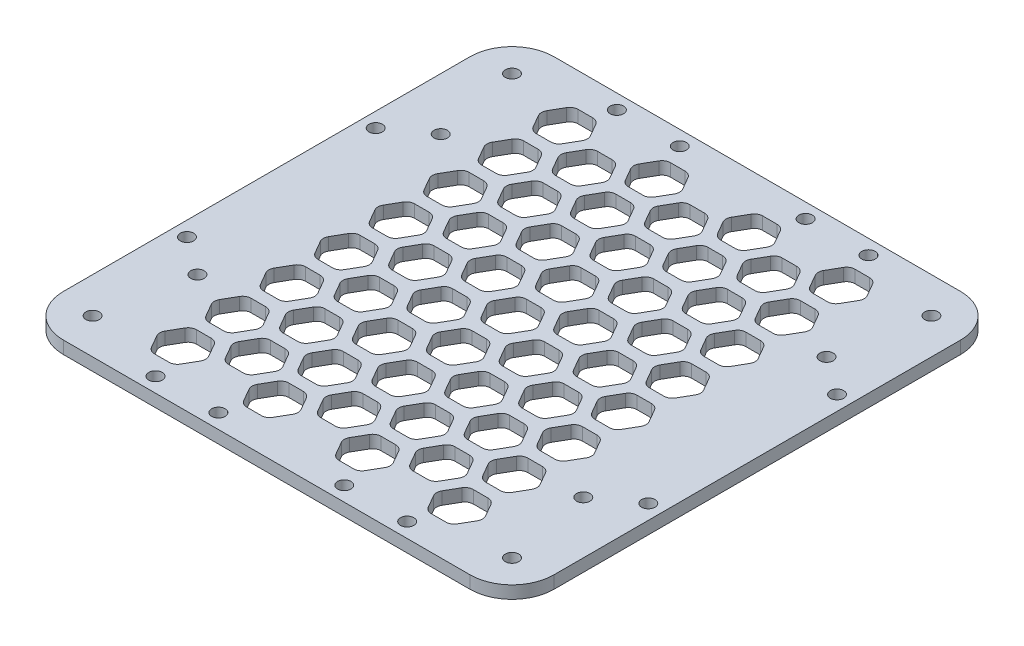
SolidWorks part; units mm, degrees
material "Thornel Mat VMA"
ref_plane "前视基准面" through (0, 0, 0) normal (0, 0, 1) x (1, 0, 0)
ref_plane "上视基准面" through (0, 0, 0) normal (0, 1, 0) x (1, 0, 0)
ref_plane "右视基准面" through (0, 0, 0) normal (1, 0, 0) x (0, 0, -1)
other "Configuration Table"
sketch "草图1" plane through (0, 0, 0) normal (0, 1, 0) x (1, 0, 0)
  line L1 (35, -46) -> (-35, -46) construction
  line L2 (35, -46) -> (35, 46) construction
  line L3 (35, 46) -> (-35, 46) construction
  line L4 (-35, -46) -> (-35, 46) construction
  line L5 (35, -46) -> (-35, 46) construction
  line L6 (35, 46) -> (-35, -46) construction
  line L7 (46, -29) -> (-46, -29) construction
  line L8 (46, -29) -> (46, 29) construction
  line L9 (46, 29) -> (-46, 29) construction
  line L10 (-46, -29) -> (-46, 29) construction
  line L11 (46, -29) -> (-46, 29) construction
  line L12 (46, 29) -> (-46, -29) construction
  line L13 (50, -33) -> (-50, -33)
  line L14 (50, -33) -> (50, 33)
  line L15 (50, 33) -> (-50, 33)
  line L16 (-50, -33) -> (-50, 33)
  line L17 (50, -33) -> (-50, 33) construction
  line L18 (50, 33) -> (-50, -33) construction
  line L19 (39, -50) -> (-39, -50)
  line L20 (39, -50) -> (39, 50)
  line L21 (39, 50) -> (-39, 50)
  line L22 (-39, -50) -> (-39, 50)
  line L23 (39, -50) -> (-39, 50) construction
  line L24 (39, 50) -> (-39, -50) construction
  circle A0 centre (-35, 46) radius 1.6
  circle A1 centre (35, 46) radius 1.6
  circle A2 centre (35, -46) radius 1.6
  circle A3 centre (-35, -46) radius 1.6
  circle A4 centre (-46, 29) radius 1.6
  circle A5 centre (46, 29) radius 1.6
  circle A6 centre (46, -29) radius 1.6
  circle A7 centre (-46, -29) radius 1.6
  point P0 (0, 0)
  point P10 (0, 0)
  point P19 (0, 0)
  point P24 (0, 0)
  dimension "D3" = 3.2
  dimension "D6" = 3.2
  dimension "D1" = 70
  dimension "D2" = 92
  dimension "D4" = 92
  dimension "D5" = 58
  dimension "D7" = 4
  dimension "D8" = 4
  dimension "D9" = 4
  dimension "D10" = 4
extrude "凸台-拉伸1" add sketch "草图1" along normal blind 3 contours L22 L15 L20 L21 A1 A0 | L22 L13 L20 L15 | L13 L22 L15 L16 A7 A4 | L20 L13 L14 L15 A6 A5 | L22 L19 L20 L13 A3 A2 region at (44.466, 0, 0) region at (0, 0, 41.4447) region at (0, 0, 0) region at (-44.466, 0, 0) region at (0, 0, -41.4447)
sketch "草图2" plane through (0, 3, 0) normal (0, 1, 0) x (1, 0, 0)
  line L1 (25, -46) -> (-25, -46) construction
  line L2 (25, -46) -> (25, 46) construction
  line L3 (25, 46) -> (-25, 46) construction
  line L4 (-25, -46) -> (-25, 46) construction
  line L5 (25, -46) -> (-25, 46) construction
  line L6 (25, 46) -> (-25, -46) construction
  circle A0 centre (-25, 46) radius 1.5
  circle A1 centre (25, 46) radius 1.5
  circle A2 centre (25, -46) radius 1.5
  circle A3 centre (-25, -46) radius 1.5
  point P0 (0, 0)
  dimension "D3" = 3
  dimension "D1" = 50
  dimension "D2" = 92
extrude "切除-拉伸1" cut sketch "草图2" against normal through all
fillet "圆角3" radius 3 4 edges at (39, 1.5, 33) (-39, 1.5, 33) (39, 1.5, -33) (-39, 1.5, -33)
fillet "圆角4" radius 3 8 edges at (50, 1.5, -33) (50, 1.5, 33) (-50, 1.5, 33) (-50, 1.5, -33) (39, 1.5, 50) (-39, 1.5, 50) (39, 1.5, -50) (-39, 1.5, -50)
sketch "草图3" plane through (0, 3, 0) normal (0, 1, 0) x (1, 0, 0)
  line L0 (-28.5, 60) -> (-28.5, 50)
  line L1 (36, 50) -> (-36, 50) construction
  line L2 (-28.5, 50) -> (-21.5, 50)
  line L3 (-21.5, 50) -> (-21.5, 60)
  line L4 (0, 0) -> (0, 22.0332) construction
  line L5 (0, 0) -> (28.908, 0) construction
  line L6 (21.5, 50) -> (21.5, 60)
  line L7 (28.5, 50) -> (21.5, 50)
  line L8 (28.5, 60) -> (28.5, 50)
  line L9 (28.5, -60) -> (28.5, -50)
  line L10 (28.5, -50) -> (21.5, -50)
  line L11 (21.5, -50) -> (21.5, -60)
  line L12 (-21.5, -50) -> (-21.5, -60)
  line L13 (-28.5, -50) -> (-21.5, -50)
  line L14 (-28.5, -60) -> (-28.5, -50)
  circle A0 centre (-25, 60) radius 1.5
  circle A1 centre (-25, 60) radius 3.5
  circle A2 centre (25, 60) radius 3.5
  circle A3 centre (25, 60) radius 1.5
  circle A4 centre (25, -60) radius 1.5
  circle A5 centre (25, -60) radius 3.5
  circle A6 centre (-25, -60) radius 3.5
  circle A7 centre (-25, -60) radius 1.5
  point P11 (-25, 46)
  point P18 (25, 46)
  point P29 (25, -46)
  point P30 (-25, -46)
  line M14 (-36, -50) -> (36, -50)
  line M20 (36, 50) -> (-36, 50)
  dimension "D1" = 3
  dimension "D2" = 7
  dimension "D3" = 120
extrude "凸台-拉伸2" [suppressed] add sketch "草图3" against normal up to surface (3 mm away) contours A1 L0 L3 M20 | A1 A0 | A2 A3 | L8 A2 L6 M20 | L14 A6 L12 M14 | A6 A7 | A5 L9 L11 M14 | A5 A4
fillet "圆角1" [suppressed] radius 3
sketch "草图4" plane through (0, 3, 0) normal (0, 1, 0) x (1, 0, 0)
  line L0 (-55, 26) -> (-50, 26)
  line L1 (-50, -30) -> (-50, 30) construction
  line L2 (-50, 26) -> (-50, 19)
  line L3 (-50, 19) -> (-55, 19)
  line L4 (0, 0) -> (0, 24.8349) construction
  line L5 (0, 0) -> (29.8822, 0) construction
  line L6 (50, 19) -> (55, 19)
  line L7 (50, 26) -> (50, 19)
  line L8 (55, 26) -> (50, 26)
  line L9 (55, -26) -> (50, -26)
  line L10 (50, -26) -> (50, -19)
  line L11 (50, -19) -> (55, -19)
  line L12 (-50, -19) -> (-55, -19)
  line L13 (-50, -26) -> (-50, -19)
  line L14 (-55, -26) -> (-50, -26)
  circle A0 centre (-55, 22.5) radius 3.5
  circle A1 centre (-55, 22.5) radius 1.6
  circle A2 centre (55, 22.5) radius 1.6
  circle A3 centre (55, 22.5) radius 3.5
  circle A4 centre (55, -22.5) radius 3.5
  circle A5 centre (55, -22.5) radius 1.6
  circle A6 centre (-55, -22.5) radius 1.6
  circle A7 centre (-55, -22.5) radius 3.5
  dimension "D1" = 3.2
  dimension "D2" = 7
  dimension "D3" = 110
  dimension "D4" = 45
extrude "凸台-拉伸3" add sketch "草图4" against normal up to surface (3 mm away) contours A0 A1 | A0 L3 L2 L0 | L6 A3 L8 L7 | A3 A2 | L12 A7 L14 L13 | A7 A6 | A4 L11 L10 L9 | A4 A5 region at (-51.2611, 3, -22.5) region at (-52.5951, 3, -24.9049) region at (51.2611, 3, -22.5) region at (51.599, 3, -22.5) region at (51.2611, 3, 22.5) region at (51.599, 3, 22.5) region at (-51.2611, 3, 22.5) region at (-52.5951, 3, 20.0951) up to face at (-25, 0, 47.5)
fillet "圆角2" radius 3 8 edges at (50, 1.5, 26) (50, 1.5, 19) (50, 1.5, -19) (50, 1.5, -26) (-50, 1.5, 26) (-50, 1.5, 19) (-50, 1.5, -19) (-50, 1.5, -26)
sketch "草图6" plane through (0, 3, 0) normal (0, 1, 0) x (1, 0, 0)
  line L1 (58.5, -58.5) -> (-58.5, -58.5)
  line L2 (58.5, -58.5) -> (58.5, 58.5)
  line L3 (58.5, 58.5) -> (-58.5, 58.5)
  line L4 (-58.5, -58.5) -> (-58.5, 58.5)
  line L5 (58.5, -58.5) -> (-58.5, 58.5) construction
  line L6 (58.5, 58.5) -> (-58.5, -58.5) construction
  line L24 (-36, -50) -> (36, -50)
  line L25 (39, -47) -> (39, -36)
  line L26 (42, -33) -> (47, -33)
  line L27 (50, -30) -> (50, -29)
  line L28 (53, -26) -> (55, -26)
  line L29 (55, -19) -> (53, -19)
  line L30 (50, -16) -> (50, 16)
  line L31 (53, 19) -> (55, 19)
  line L32 (55, 26) -> (53, 26)
  line L33 (50, 29) -> (50, 30)
  line L34 (47, 33) -> (42, 33)
  line L35 (39, 36) -> (39, 47)
  line L36 (36, 50) -> (-36, 50)
  line L37 (-39, 47) -> (-39, 36)
  line L38 (-42, 33) -> (-47, 33)
  line L39 (-50, 30) -> (-50, 29)
  line L40 (-53, 26) -> (-55, 26)
  line L41 (-55, 19) -> (-53, 19)
  line L42 (-50, 16) -> (-50, -16)
  line L43 (-53, -19) -> (-55, -19)
  line L44 (-55, -26) -> (-53, -26)
  line L45 (-50, -29) -> (-50, -30)
  line L46 (-47, -33) -> (-42, -33)
  line L47 (-39, -36) -> (-39, -47)
  line L48 (-36, -50) -> (36, -50)
  line L49 (39, -47) -> (39, -36)
  line L50 (42, -33) -> (47, -33)
  line L51 (50, -30) -> (50, -29)
  line L52 (53, -26) -> (55, -26)
  line L53 (55, -19) -> (53, -19)
  line L54 (50, -16) -> (50, 16)
  line L55 (53, 19) -> (55, 19)
  line L56 (55, 26) -> (53, 26)
  line L57 (50, 29) -> (50, 30)
  line L58 (47, 33) -> (42, 33)
  line L59 (39, 36) -> (39, 47)
  line L60 (36, 50) -> (-36, 50)
  line L61 (-39, 47) -> (-39, 36)
  line L62 (-42, 33) -> (-47, 33)
  line L63 (-50, 30) -> (-50, 29)
  line L64 (-53, 26) -> (-55, 26)
  line L65 (-55, 19) -> (-53, 19)
  line L66 (-50, 16) -> (-50, -16)
  line L67 (-53, -19) -> (-55, -19)
  line L68 (-55, -26) -> (-53, -26)
  line L69 (-50, -29) -> (-50, -30)
  line L70 (-47, -33) -> (-42, -33)
  line L71 (-39, -36) -> (-39, -47)
  circle A0 centre (-35, 46) radius 1.6 construction
  circle A1 centre (-35, 46) radius 1.6
  circle A2 centre (-25, 46) radius 1.5 construction
  circle A3 centre (-25, 46) radius 1.5
  circle A4 centre (25, 46) radius 1.5 construction
  circle A5 centre (25, 46) radius 1.5
  circle A6 centre (35, 46) radius 1.6 construction
  circle A7 centre (35, 46) radius 1.6
  circle A8 centre (35, -46) radius 1.6 construction
  circle A9 centre (25, -46) radius 1.5 construction
  circle A10 centre (-25, -46) radius 1.5 construction
  circle A11 centre (-35, -46) radius 1.6 construction
  circle A12 centre (35, -46) radius 1.6
  circle A13 centre (25, -46) radius 1.5
  circle A14 centre (-25, -46) radius 1.5
  circle A15 centre (-35, -46) radius 1.6
  arc A24 (36, -50) -> (39, -47) centre (36, -47) ccw
  arc A25 (42, -33) -> (39, -36) centre (42, -36) ccw
  arc A26 (47, -33) -> (50, -30) centre (47, -30) ccw
  arc A27 (53, -26) -> (50, -29) centre (53, -29) ccw
  arc A28 (55, -26) -> (55, -19) centre (55, -22.5) ccw
  arc A29 (50, -16) -> (53, -19) centre (53, -16) ccw
  arc A30 (53, 19) -> (50, 16) centre (53, 16) ccw
  arc A31 (55, 19) -> (55, 26) centre (55, 22.5) ccw
  arc A32 (50, 29) -> (53, 26) centre (53, 29) ccw
  arc A33 (50, 30) -> (47, 33) centre (47, 30) ccw
  arc A34 (39, 36) -> (42, 33) centre (42, 36) ccw
  arc A35 (39, 47) -> (36, 50) centre (36, 47) ccw
  arc A36 (-36, 50) -> (-39, 47) centre (-36, 47) ccw
  arc A37 (-42, 33) -> (-39, 36) centre (-42, 36) ccw
  arc A38 (-47, 33) -> (-50, 30) centre (-47, 30) ccw
  arc A39 (-53, 26) -> (-50, 29) centre (-53, 29) ccw
  arc A40 (-55, 26) -> (-55, 19) centre (-55, 22.5) ccw
  arc A41 (-50, 16) -> (-53, 19) centre (-53, 16) ccw
  arc A42 (-53, -19) -> (-50, -16) centre (-53, -16) ccw
  arc A43 (-55, -19) -> (-55, -26) centre (-55, -22.5) ccw
  arc A44 (-50, -29) -> (-53, -26) centre (-53, -29) ccw
  arc A45 (-50, -30) -> (-47, -33) centre (-47, -30) ccw
  arc A46 (-39, -36) -> (-42, -33) centre (-42, -36) ccw
  arc A47 (-39, -47) -> (-36, -50) centre (-36, -47) ccw
  arc A48 (36, -50) -> (39, -47) centre (36, -47) ccw
  arc A49 (42, -33) -> (39, -36) centre (42, -36) ccw
  arc A50 (47, -33) -> (50, -30) centre (47, -30) ccw
  arc A51 (53, -26) -> (50, -29) centre (53, -29) ccw
  arc A52 (55, -26) -> (55, -19) centre (55, -22.5) ccw
  arc A53 (50, -16) -> (53, -19) centre (53, -16) ccw
  arc A54 (53, 19) -> (50, 16) centre (53, 16) ccw
  arc A55 (55, 19) -> (55, 26) centre (55, 22.5) ccw
  arc A56 (50, 29) -> (53, 26) centre (53, 29) ccw
  arc A57 (50, 30) -> (47, 33) centre (47, 30) ccw
  arc A58 (39, 36) -> (42, 33) centre (42, 36) ccw
  arc A59 (39, 47) -> (36, 50) centre (36, 47) ccw
  arc A60 (-36, 50) -> (-39, 47) centre (-36, 47) ccw
  arc A61 (-42, 33) -> (-39, 36) centre (-42, 36) ccw
  arc A62 (-47, 33) -> (-50, 30) centre (-47, 30) ccw
  arc A63 (-53, 26) -> (-50, 29) centre (-53, 29) ccw
  arc A64 (-55, 26) -> (-55, 19) centre (-55, 22.5) ccw
  arc A65 (-50, 16) -> (-53, 19) centre (-53, 16) ccw
  arc A66 (-53, -19) -> (-50, -16) centre (-53, -16) ccw
  arc A67 (-55, -19) -> (-55, -26) centre (-55, -22.5) ccw
  arc A68 (-50, -29) -> (-53, -26) centre (-53, -29) ccw
  arc A69 (-50, -30) -> (-47, -33) centre (-47, -30) ccw
  arc A70 (-39, -36) -> (-42, -33) centre (-42, -36) ccw
  arc A71 (-39, -47) -> (-36, -50) centre (-36, -47) ccw
  point P2 (0, 0)
  dimension "D1" = 0
extrude "凸台-拉伸4" add sketch "草图6" against normal up to surface (3 mm away) contours A64 L64 A63 L63 A62 L62 A61 L61 A60 L60 A59 L59 A58 L58 A57 L57 A56 L56 A55 L2 L3 L4 | A71 L71 A70 L70 A69 L69 A68 L68 A67 L4 L1 L2 A52 L52 A51 L51 A50 L50 A49 L49 A48 L48 | A1 | A3 | A5 | A7 | A15 | A14 | A13 | A12 region at (0, 3, 57.2759) region at (58.3405, 3, -25.8405) region at (-35, 3, -46) region at (-25, 3, -46) region at (25, 3, -46) region at (35, 3, -46) region at (35, 3, 46) region at (25, 3, 46) region at (-25, 3, 46) region at (-35, 3, 46) up to face at (-25, 0, 47.5)
sketch "草图7" plane through (0, 3, 0) normal (0, 1, 0) x (1, 0, 0)
  line L1 (50, -50) -> (-50, -50) construction
  line L2 (50, -50) -> (50, 50) construction
  line L3 (50, 50) -> (-50, 50) construction
  line L4 (-50, -50) -> (-50, 50) construction
  line L5 (50, -50) -> (-50, 50) construction
  line L6 (50, 50) -> (-50, -50) construction
  circle A0 centre (-50, 50) radius 1.6
  circle A1 centre (50, 50) radius 1.6
  circle A2 centre (50, -50) radius 1.6
  circle A3 centre (-50, -50) radius 1.6
  point P0 (0, 0)
  point P16 (0, 0)
  dimension "D2" = 3.2
  dimension "D1" = 100
  dimension "D3" = 4
extrude "切除-拉伸4" cut sketch "草图7" against normal through all
fillet "圆角5" radius 10 4 edges at (58.5, 1.5, 58.5) (-58.5, 1.5, 58.5) (58.5, 1.5, -58.5) (-58.5, 1.5, -58.5)
sketch "草图5" plane through (0, 3, 0) normal (0, 1, 0) x (1, 0, 0)
  line L0 (-50, -16) -> (-50, 16) construction
  line L1 (-36.4641, 49.5) -> (-38.1962, 46.5)
  line L2 (-38.1962, 44.5) -> (-36.4641, 41.5)
  line L3 (-34.7321, 40.5) -> (-31.2679, 40.5)
  line L4 (-29.5359, 41.5) -> (-27.8038, 44.5)
  line L5 (-27.8038, 46.5) -> (-29.5359, 49.5)
  line L6 (-31.2679, 50.5) -> (-34.7321, 50.5)
  line L7 (-18.5359, 35.1491) -> (-16.8038, 38.1491)
  line L8 (-16.8038, 40.1491) -> (-18.5359, 43.1491)
  line L9 (-20.2679, 44.1491) -> (-23.7321, 44.1491)
  line L10 (-25.4641, 43.1491) -> (-27.1962, 40.1491)
  line L11 (-27.1962, 38.1491) -> (-25.4641, 35.1491)
  line L12 (-23.7321, 34.1491) -> (-20.2679, 34.1491)
  line L13 (29.5359, 49.5) -> (27.8038, 46.5)
  line L14 (-33, 45.5) -> (-22, 39.1491) construction
  line L15 (-14.4641, 49.5) -> (-16.1962, 46.5)
  line L16 (-16.1962, 44.5) -> (-14.4641, 41.5)
  line L17 (-12.7321, 40.5) -> (-9.2679, 40.5)
  line L18 (-7.5359, 41.5) -> (-5.8038, 44.5)
  line L19 (-5.8038, 46.5) -> (-7.5359, 49.5)
  line L20 (-9.2679, 50.5) -> (-12.7321, 50.5)
  line L21 (3.4641, 35.1491) -> (5.1962, 38.1491)
  line L22 (5.1962, 40.1491) -> (3.4641, 43.1491)
  line L23 (1.7321, 44.1491) -> (-1.7321, 44.1491)
  line L24 (-3.4641, 43.1491) -> (-5.1962, 40.1491)
  line L25 (-5.1962, 38.1491) -> (-3.4641, 35.1491)
  line L26 (-1.7321, 34.1491) -> (1.7321, 34.1491)
  line L27 (-11, 45.5) -> (0, 39.1491) construction
  line L28 (7.5359, 49.5) -> (5.8038, 46.5)
  line L29 (5.8038, 44.5) -> (7.5359, 41.5)
  line L30 (9.2679, 40.5) -> (12.7321, 40.5)
  line L31 (14.4641, 41.5) -> (16.1962, 44.5)
  line L32 (16.1962, 46.5) -> (14.4641, 49.5)
  line L33 (12.7321, 50.5) -> (9.2679, 50.5)
  line L34 (25.4641, 35.1491) -> (27.1962, 38.1491)
  line L35 (27.1962, 40.1491) -> (25.4641, 43.1491)
  line L36 (23.7321, 44.1491) -> (20.2679, 44.1491)
  line L37 (18.5359, 43.1491) -> (16.8038, 40.1491)
  line L38 (16.8038, 38.1491) -> (18.5359, 35.1491)
  line L39 (20.2679, 34.1491) -> (23.7321, 34.1491)
  line L40 (11, 45.5) -> (22, 39.1491) construction
  line L41 (-14.4641, 36.5) -> (-16.1962, 33.5)
  line L42 (-16.1962, 31.5) -> (-14.4641, 28.5)
  line L43 (-12.7321, 27.5) -> (-9.2679, 27.5)
  line L44 (-7.5359, 28.5) -> (-5.8038, 31.5)
  line L45 (-5.8038, 33.5) -> (-7.5359, 36.5)
  line L46 (-9.2679, 37.5) -> (-12.7321, 37.5)
  line L47 (3.4641, 22.1491) -> (5.1962, 25.1491)
  line L48 (5.1962, 27.1491) -> (3.4641, 30.1491)
  line L49 (1.7321, 31.1491) -> (-1.7321, 31.1491)
  line L50 (-3.4641, 30.1491) -> (-5.1962, 27.1491)
  line L51 (-5.1962, 25.1491) -> (-3.4641, 22.1491)
  line L52 (-1.7321, 21.1491) -> (1.7321, 21.1491)
  line L53 (-11, 32.5) -> (0, 26.1491) construction
  line L54 (7.5359, 36.5) -> (5.8038, 33.5)
  line L55 (5.8038, 31.5) -> (7.5359, 28.5)
  line L56 (9.2679, 27.5) -> (12.7321, 27.5)
  line L57 (14.4641, 28.5) -> (16.1962, 31.5)
  line L58 (16.1962, 33.5) -> (14.4641, 36.5)
  line L59 (12.7321, 37.5) -> (9.2679, 37.5)
  line L60 (25.4641, 22.1491) -> (27.1962, 25.1491)
  line L61 (27.1962, 27.1491) -> (25.4641, 30.1491)
  line L62 (23.7321, 31.1491) -> (20.2679, 31.1491)
  line L63 (18.5359, 30.1491) -> (16.8038, 27.1491)
  line L64 (16.8038, 25.1491) -> (18.5359, 22.1491)
  line L65 (20.2679, 21.1491) -> (23.7321, 21.1491)
  line L66 (11, 32.5) -> (22, 26.1491) construction
  line L67 (-14.4641, 23.5) -> (-16.1962, 20.5)
  line L68 (-16.1962, 18.5) -> (-14.4641, 15.5)
  line L69 (-12.7321, 14.5) -> (-9.2679, 14.5)
  line L70 (-7.5359, 15.5) -> (-5.8038, 18.5)
  line L71 (-5.8038, 20.5) -> (-7.5359, 23.5)
  line L72 (-9.2679, 24.5) -> (-12.7321, 24.5)
  line L73 (3.4641, 9.1491) -> (5.1962, 12.1491)
  line L74 (5.1962, 14.1491) -> (3.4641, 17.1491)
  line L75 (1.7321, 18.1491) -> (-1.7321, 18.1491)
  line L76 (-3.4641, 17.1491) -> (-5.1962, 14.1491)
  line L77 (-5.1962, 12.1491) -> (-3.4641, 9.1491)
  line L78 (-1.7321, 8.1491) -> (1.7321, 8.1491)
  line L79 (-11, 19.5) -> (0, 13.1491) construction
  line L80 (7.5359, 23.5) -> (5.8038, 20.5)
  line L81 (5.8038, 18.5) -> (7.5359, 15.5)
  line L82 (9.2679, 14.5) -> (12.7321, 14.5)
  line L83 (14.4641, 15.5) -> (16.1962, 18.5)
  line L84 (16.1962, 20.5) -> (14.4641, 23.5)
  line L85 (12.7321, 24.5) -> (9.2679, 24.5)
  line L86 (25.4641, 9.1491) -> (27.1962, 12.1491)
  line L87 (27.1962, 14.1491) -> (25.4641, 17.1491)
  line L88 (23.7321, 18.1491) -> (20.2679, 18.1491)
  line L89 (18.5359, 17.1491) -> (16.8038, 14.1491)
  line L90 (16.8038, 12.1491) -> (18.5359, 9.1491)
  line L91 (20.2679, 8.1491) -> (23.7321, 8.1491)
  line L92 (11, 19.5) -> (22, 13.1491) construction
  line L93 (-14.4641, 10.5) -> (-16.1962, 7.5)
  line L94 (-16.1962, 5.5) -> (-14.4641, 2.5)
  line L95 (-12.7321, 1.5) -> (-9.2679, 1.5)
  line L96 (-7.5359, 2.5) -> (-5.8038, 5.5)
  line L97 (-5.8038, 7.5) -> (-7.5359, 10.5)
  line L98 (-9.2679, 11.5) -> (-12.7321, 11.5)
  line L99 (3.4641, -3.8509) -> (5.1962, -0.8509)
  line L100 (5.1962, 1.1491) -> (3.4641, 4.1491)
  line L101 (1.7321, 5.1491) -> (-1.7321, 5.1491)
  line L102 (-3.4641, 4.1491) -> (-5.1962, 1.1491)
  line L103 (-5.1962, -0.8509) -> (-3.4641, -3.8509)
  line L104 (-1.7321, -4.8509) -> (1.7321, -4.8509)
  line L105 (-11, 6.5) -> (0, 0.1491) construction
  line L106 (7.5359, 10.5) -> (5.8038, 7.5)
  line L107 (5.8038, 5.5) -> (7.5359, 2.5)
  line L108 (9.2679, 1.5) -> (12.7321, 1.5)
  line L109 (14.4641, 2.5) -> (16.1962, 5.5)
  line L110 (16.1962, 7.5) -> (14.4641, 10.5)
  line L111 (12.7321, 11.5) -> (9.2679, 11.5)
  line L112 (25.4641, -3.8509) -> (27.1962, -0.8509)
  line L113 (27.1962, 1.1491) -> (25.4641, 4.1491)
  line L114 (23.7321, 5.1491) -> (20.2679, 5.1491)
  line L115 (18.5359, 4.1491) -> (16.8038, 1.1491)
  line L116 (16.8038, -0.8509) -> (18.5359, -3.8509)
  line L117 (20.2679, -4.8509) -> (23.7321, -4.8509)
  line L118 (11, 6.5) -> (22, 0.1491) construction
  line L119 (-14.4641, -2.5) -> (-16.1962, -5.5)
  line L120 (-16.1962, -7.5) -> (-14.4641, -10.5)
  line L121 (-12.7321, -11.5) -> (-9.2679, -11.5)
  line L122 (-7.5359, -10.5) -> (-5.8038, -7.5)
  line L123 (-5.8038, -5.5) -> (-7.5359, -2.5)
  line L124 (-9.2679, -1.5) -> (-12.7321, -1.5)
  line L125 (3.4641, -16.8509) -> (5.1962, -13.8509)
  line L126 (5.1962, -11.8509) -> (3.4641, -8.8509)
  line L127 (1.7321, -7.8509) -> (-1.7321, -7.8509)
  line L128 (-3.4641, -8.8509) -> (-5.1962, -11.8509)
  line L129 (-5.1962, -13.8509) -> (-3.4641, -16.8509)
  line L130 (-1.7321, -17.8509) -> (1.7321, -17.8509)
  line L131 (-11, -6.5) -> (0, -12.8509) construction
  line L132 (7.5359, -2.5) -> (5.8038, -5.5)
  line L133 (5.8038, -7.5) -> (7.5359, -10.5)
  line L134 (9.2679, -11.5) -> (12.7321, -11.5)
  line L135 (14.4641, -10.5) -> (16.1962, -7.5)
  line L136 (16.1962, -5.5) -> (14.4641, -2.5)
  line L137 (12.7321, -1.5) -> (9.2679, -1.5)
  line L138 (25.4641, -16.8509) -> (27.1962, -13.8509)
  line L139 (27.1962, -11.8509) -> (25.4641, -8.8509)
  line L140 (23.7321, -7.8509) -> (20.2679, -7.8509)
  line L141 (18.5359, -8.8509) -> (16.8038, -11.8509)
  line L142 (16.8038, -13.8509) -> (18.5359, -16.8509)
  line L143 (20.2679, -17.8509) -> (23.7321, -17.8509)
  line L144 (11, -6.5) -> (22, -12.8509) construction
  line L145 (-14.4641, -15.5) -> (-16.1962, -18.5)
  line L146 (-16.1962, -20.5) -> (-14.4641, -23.5)
  line L147 (-12.7321, -24.5) -> (-9.2679, -24.5)
  line L148 (-7.5359, -23.5) -> (-5.8038, -20.5)
  line L149 (-5.8038, -18.5) -> (-7.5359, -15.5)
  line L150 (-9.2679, -14.5) -> (-12.7321, -14.5)
  line L157 (-11, -19.5) -> (-6.6699, -22) construction
  line L158 (7.5359, -15.5) -> (5.8038, -18.5)
  line L159 (5.8038, -20.5) -> (7.5359, -23.5)
  line L160 (9.2679, -24.5) -> (12.7321, -24.5)
  line L161 (14.4641, -23.5) -> (16.1962, -20.5)
  line L162 (16.1962, -18.5) -> (14.4641, -15.5)
  line L163 (12.7321, -14.5) -> (9.2679, -14.5)
  line L170 (11, -19.5) -> (15.3301, -22) construction
  line L171 (-36.4641, 36.5) -> (-38.1962, 33.5)
  line L172 (-38.1962, 31.5) -> (-36.4641, 28.5)
  line L173 (-34.7321, 27.5) -> (-31.2679, 27.5)
  line L174 (-29.5359, 28.5) -> (-27.8038, 31.5)
  line L175 (-27.8038, 33.5) -> (-29.5359, 36.5)
  line L176 (-31.2679, 37.5) -> (-34.7321, 37.5)
  line L177 (-18.5359, 22.1491) -> (-16.8038, 25.1491)
  line L178 (-16.8038, 27.1491) -> (-18.5359, 30.1491)
  line L179 (-20.2679, 31.1491) -> (-23.7321, 31.1491)
  line L180 (-25.4641, 30.1491) -> (-27.1962, 27.1491)
  line L181 (-27.1962, 25.1491) -> (-25.4641, 22.1491)
  line L182 (-23.7321, 21.1491) -> (-20.2679, 21.1491)
  line L183 (-33, 32.5) -> (-22, 26.1491) construction
  line L184 (-36.4641, 23.5) -> (-38.1962, 20.5)
  line L185 (-38.1962, 18.5) -> (-36.4641, 15.5)
  line L186 (-34.7321, 14.5) -> (-31.2679, 14.5)
  line L187 (-29.5359, 15.5) -> (-27.8038, 18.5)
  line L188 (-27.8038, 20.5) -> (-29.5359, 23.5)
  line L189 (-31.2679, 24.5) -> (-34.7321, 24.5)
  line L190 (-18.5359, 9.1491) -> (-16.8038, 12.1491)
  line L191 (-16.8038, 14.1491) -> (-18.5359, 17.1491)
  line L192 (-20.2679, 18.1491) -> (-23.7321, 18.1491)
  line L193 (-25.4641, 17.1491) -> (-27.1962, 14.1491)
  line L194 (-27.1962, 12.1491) -> (-25.4641, 9.1491)
  line L195 (-23.7321, 8.1491) -> (-20.2679, 8.1491)
  line L196 (-33, 19.5) -> (-22, 13.1491) construction
  line L197 (-36.4641, 10.5) -> (-38.1962, 7.5)
  line L198 (-38.1962, 5.5) -> (-36.4641, 2.5)
  line L199 (-34.7321, 1.5) -> (-31.2679, 1.5)
  line L200 (-29.5359, 2.5) -> (-27.8038, 5.5)
  line L201 (-27.8038, 7.5) -> (-29.5359, 10.5)
  line L202 (-31.2679, 11.5) -> (-34.7321, 11.5)
  line L203 (-18.5359, -3.8509) -> (-16.8038, -0.8509)
  line L204 (-16.8038, 1.1491) -> (-18.5359, 4.1491)
  line L205 (-20.2679, 5.1491) -> (-23.7321, 5.1491)
  line L206 (-25.4641, 4.1491) -> (-27.1962, 1.1491)
  line L207 (-27.1962, -0.8509) -> (-25.4641, -3.8509)
  line L208 (-23.7321, -4.8509) -> (-20.2679, -4.8509)
  line L209 (-33, 6.5) -> (-22, 0.1491) construction
  line L210 (-36.4641, -2.5) -> (-38.1962, -5.5)
  line L211 (-38.1962, -7.5) -> (-36.4641, -10.5)
  line L212 (-34.7321, -11.5) -> (-31.2679, -11.5)
  line L213 (-29.5359, -10.5) -> (-27.8038, -7.5)
  line L214 (-27.8038, -5.5) -> (-29.5359, -2.5)
  line L215 (-31.2679, -1.5) -> (-34.7321, -1.5)
  line L216 (-18.5359, -16.8509) -> (-16.8038, -13.8509)
  line L217 (-16.8038, -11.8509) -> (-18.5359, -8.8509)
  line L218 (-20.2679, -7.8509) -> (-23.7321, -7.8509)
  line L219 (-25.4641, -8.8509) -> (-27.1962, -11.8509)
  line L220 (-27.1962, -13.8509) -> (-25.4641, -16.8509)
  line L221 (-23.7321, -17.8509) -> (-20.2679, -17.8509)
  line L222 (-33, -6.5) -> (-22, -12.8509) construction
  line L223 (-36.4641, -15.5) -> (-38.1962, -18.5)
  line L224 (-38.1962, -20.5) -> (-36.4641, -23.5)
  line L225 (-34.7321, -24.5) -> (-31.2679, -24.5)
  line L226 (-29.5359, -23.5) -> (-27.8038, -20.5)
  line L227 (-27.8038, -18.5) -> (-29.5359, -15.5)
  line L228 (-31.2679, -14.5) -> (-34.7321, -14.5)
  line L235 (-33, -19.5) -> (-28.6699, -22) construction
  line L236 (-25.4641, -21.8509) -> (-27.1962, -24.8509) [skipped]
  line L237 (-20.2679, -20.8509) -> (-23.7321, -20.8509) [skipped]
  line L238 (-8.8422, -38.6409) -> (-9.7082, -37.1409) [skipped]
  line L239 (-18.5359, -29.8509) -> (-16.8038, -26.8509) [skipped]
  line L240 (-18.7321, -30.8509) -> (-17, -30.8509) [skipped]
  line L241 (-9.7918, -32.8108) -> (-10.6578, -34.3108) [skipped]
  line L242 (6.7321, -20.8509) -> (5, -20.8509) [skipped]
  line L243 (13.1578, -38.6409) -> (12.2918, -37.1409) [skipped]
  line L244 (3.4641, -29.8509) -> (5.1962, -26.8509) [skipped]
  line L245 (5, -30.8509) -> (6.7321, -30.8509) [skipped]
  line L246 (2.7655, -40.6409) -> (3.6316, -42.1409) [skipped]
  line L247 (-18.3684, -42.1409) -> (-17.5024, -43.6409) [skipped]
  line L248 (48.5, 58.5) -> (-48.5, 58.5) construction
  line L249 (13.0742, -31.3108) -> (12.2082, -32.8108) [skipped]
  line L250 (28.7321, -20.8509) -> (27, -20.8509) [skipped]
  line L251 (35.1578, -38.6409) -> (34.2918, -37.1409) [skipped]
  line L252 (16.8038, -26.8509) -> (18.5359, -29.8509) [skipped]
  line L253 (25.4641, -29.8509) -> (27.1962, -26.8509) [skipped]
  line L254 (20.2679, -30.8509) -> (23.7321, -30.8509) [skipped]
  line L255 (27.8038, 44.5) -> (29.5359, 41.5)
  line L256 (31.2679, 40.5) -> (34.7321, 40.5)
  line L257 (36.4641, 41.5) -> (38.1962, 44.5)
  line L258 (38.1962, 46.5) -> (36.4641, 49.5)
  line L259 (34.7321, 50.5) -> (31.2679, 50.5)
  line L266 (-18.5359, -29.8509) -> (-16.8038, -26.8509)
  line L267 (29.5359, 36.5) -> (27.8038, 33.5)
  line L268 (27.8038, 31.5) -> (29.5359, 28.5)
  line L269 (31.2679, 27.5) -> (34.7321, 27.5)
  line L270 (36.4641, 28.5) -> (38.1962, 31.5)
  line L271 (38.1962, 33.5) -> (36.4641, 36.5)
  line L272 (34.7321, 37.5) -> (31.2679, 37.5)
  line L279 (-16.8038, -24.8509) -> (-18.5359, -21.8509)
  line L280 (29.5359, 23.5) -> (27.8038, 20.5)
  line L281 (27.8038, 18.5) -> (29.5359, 15.5)
  line L282 (31.2679, 14.5) -> (34.7321, 14.5)
  line L283 (36.4641, 15.5) -> (38.1962, 18.5)
  line L284 (38.1962, 20.5) -> (36.4641, 23.5)
  line L285 (34.7321, 24.5) -> (31.2679, 24.5)
  line L292 (-25.4641, -21.8509) -> (-27.1962, -24.8509)
  line L293 (29.5359, 10.5) -> (27.8038, 7.5)
  line L294 (27.8038, 5.5) -> (29.5359, 2.5)
  line L295 (31.2679, 1.5) -> (34.7321, 1.5)
  line L296 (36.4641, 2.5) -> (38.1962, 5.5)
  line L297 (38.1962, 7.5) -> (36.4641, 10.5)
  line L298 (34.7321, 11.5) -> (31.2679, 11.5)
  line L305 (-27.1962, -26.8509) -> (-25.4641, -29.8509)
  line L306 (29.5359, -2.5) -> (27.8038, -5.5)
  line L307 (27.8038, -7.5) -> (29.5359, -10.5)
  line L308 (31.2679, -11.5) -> (34.7321, -11.5)
  line L309 (36.4641, -10.5) -> (38.1962, -7.5)
  line L310 (38.1962, -5.5) -> (36.4641, -2.5)
  line L311 (34.7321, -1.5) -> (31.2679, -1.5)
  line L318 (-33, -19.5) -> (-22, -25.8509) construction
  line L319 (29.5359, -15.5) -> (27.8038, -18.5)
  line L320 (27.8038, -20.5) -> (29.5359, -23.5)
  line L321 (31.2679, -24.5) -> (34.7321, -24.5)
  line L322 (36.4641, -23.5) -> (38.1962, -20.5)
  line L323 (38.1962, -18.5) -> (36.4641, -15.5)
  line L324 (34.7321, -14.5) -> (31.2679, -14.5)
  line L331 (-20.2679, -20.8509) -> (-23.7321, -20.8509)
  line L332 (47.4641, 35.1491) -> (49.1962, 38.1491) [skipped]
  line L333 (49.1962, 40.1491) -> (47.4641, 43.1491) [skipped]
  line L334 (45.7321, 44.1491) -> (42.2679, 44.1491) [skipped]
  line L335 (40.5359, 43.1491) -> (38.8038, 40.1491) [skipped]
  line L336 (38.8038, 38.1491) -> (40.5359, 35.1491) [skipped]
  line L337 (42.2679, 34.1491) -> (45.7321, 34.1491) [skipped]
  line L338 (47.4641, 22.1491) -> (49.1962, 25.1491) [skipped]
  line L339 (49.1962, 27.1491) -> (47.4641, 30.1491) [skipped]
  line L340 (45.7321, 31.1491) -> (42.2679, 31.1491) [skipped]
  line L341 (40.5359, 30.1491) -> (38.8038, 27.1491) [skipped]
  line L342 (38.8038, 25.1491) -> (40.5359, 22.1491) [skipped]
  line L343 (42.2679, 21.1491) -> (45.7321, 21.1491) [skipped]
  line L344 (47.4641, 9.1491) -> (49.1962, 12.1491) [skipped]
  line L345 (49.1962, 14.1491) -> (47.4641, 17.1491) [skipped]
  line L346 (45.7321, 18.1491) -> (42.2679, 18.1491) [skipped]
  line L347 (40.5359, 17.1491) -> (38.8038, 14.1491) [skipped]
  line L348 (38.8038, 12.1491) -> (40.5359, 9.1491) [skipped]
  line L349 (42.2679, 8.1491) -> (45.7321, 8.1491) [skipped]
  line L350 (47.4641, -3.8509) -> (49.1962, -0.8509) [skipped]
  line L351 (49.1962, 1.1491) -> (47.4641, 4.1491) [skipped]
  line L352 (45.7321, 5.1491) -> (42.2679, 5.1491) [skipped]
  line L353 (40.5359, 4.1491) -> (38.8038, 1.1491) [skipped]
  line L354 (38.8038, -0.8509) -> (40.5359, -3.8509) [skipped]
  line L355 (42.2679, -4.8509) -> (45.7321, -4.8509) [skipped]
  line L356 (47.4641, -16.8509) -> (49.1962, -13.8509) [skipped]
  line L357 (49.1962, -11.8509) -> (47.4641, -8.8509) [skipped]
  line L358 (45.7321, -7.8509) -> (42.2679, -7.8509) [skipped]
  line L359 (40.5359, -8.8509) -> (38.8038, -11.8509) [skipped]
  line L360 (38.8038, -13.8509) -> (40.5359, -16.8509) [skipped]
  line L361 (42.2679, -17.8509) -> (45.7321, -17.8509) [skipped]
  line L362 (47.4641, -29.8509) -> (49.1962, -26.8509) [skipped]
  line L363 (49.1962, -24.8509) -> (47.4641, -21.8509) [skipped]
  line L364 (45.7321, -20.8509) -> (42.2679, -20.8509) [skipped]
  line L365 (40.5359, -21.8509) -> (38.8038, -24.8509) [skipped]
  line L366 (38.8038, -26.8509) -> (40.5359, -29.8509) [skipped]
  line L367 (42.2679, -30.8509) -> (45.7321, -30.8509) [skipped]
  line L368 (33, 45.5) -> (44, 39.1491) construction
  line L369 (33, 32.5) -> (44, 26.1491) construction
  line L370 (33, 19.5) -> (44, 13.1491) construction
  line L371 (33, 6.5) -> (44, 0.1491) construction
  line L372 (33, -6.5) -> (44, -12.8509) construction
  line L373 (33, -19.5) -> (44, -25.8509) construction
  line L374 (-23.7321, -30.8509) -> (-20.2679, -30.8509)
  line L375 (-36.4641, -28.5) -> (-38.1962, -31.5)
  line L376 (-38.1962, -33.5) -> (-36.4641, -36.5)
  line L377 (-34.7321, -37.5) -> (-31.2679, -37.5)
  line L378 (-29.5359, -36.5) -> (-27.8038, -33.5)
  line L379 (-27.8038, -31.5) -> (-29.5359, -28.5)
  line L380 (-31.2679, -27.5) -> (-34.7321, -27.5)
  line L381 (-1.7321, -30.8509) -> (1.7321, -30.8509)
  line L382 (-14.4641, -28.5) -> (-16.1962, -31.5)
  line L383 (-16.1962, -33.5) -> (-14.4641, -36.5)
  line L384 (-12.7321, -37.5) -> (-9.2679, -37.5)
  line L385 (-7.5359, -36.5) -> (-5.8038, -33.5)
  line L386 (-5.8038, -31.5) -> (-7.5359, -28.5)
  line L387 (-9.2679, -27.5) -> (-12.7321, -27.5)
  line L388 (7.5359, -28.5) -> (5.8038, -31.5)
  line L389 (5.8038, -33.5) -> (7.5359, -36.5)
  line L390 (9.2679, -37.5) -> (12.7321, -37.5)
  line L391 (14.4641, -36.5) -> (16.1962, -33.5)
  line L392 (16.1962, -31.5) -> (14.4641, -28.5)
  line L393 (12.7321, -27.5) -> (9.2679, -27.5)
  line L394 (29.5359, -28.5) -> (27.8038, -31.5)
  line L395 (27.8038, -33.5) -> (29.5359, -36.5)
  line L396 (31.2679, -37.5) -> (34.7321, -37.5)
  line L397 (36.4641, -36.5) -> (38.1962, -33.5)
  line L398 (38.1962, -31.5) -> (36.4641, -28.5)
  line L399 (34.7321, -27.5) -> (31.2679, -27.5)
  line L400 (25.4641, -29.8509) -> (27.1962, -26.8509)
  line L401 (27.1962, -24.8509) -> (25.4641, -21.8509)
  line L402 (23.7321, -20.8509) -> (20.2679, -20.8509)
  line L403 (11, -19.5) -> (22, -25.8509) construction
  line L404 (18.5359, -21.8509) -> (16.8038, -24.8509)
  line L405 (16.8038, -26.8509) -> (18.5359, -29.8509)
  line L406 (20.2679, -30.8509) -> (23.7321, -30.8509)
  line L407 (3.4641, -29.8509) -> (5.1962, -26.8509)
  line L408 (5.1962, -24.8509) -> (3.4641, -21.8509)
  line L409 (1.7321, -20.8509) -> (-1.7321, -20.8509)
  line L410 (-3.4641, -21.8509) -> (-5.1962, -24.8509)
  line L411 (-5.1962, -26.8509) -> (-3.4641, -29.8509)
  line L412 (-11, -19.5) -> (0, -25.8509) construction
  line L413 (-18.5359, -42.8509) -> (-16.8038, -39.8509)
  line L414 (-16.8038, -37.8509) -> (-18.5359, -34.8509)
  line L415 (-25.4641, -34.8509) -> (-27.1962, -37.8509)
  line L416 (-27.1962, -39.8509) -> (-25.4641, -42.8509)
  line L417 (-33, -32.5) -> (-22, -38.8509) construction
  line L418 (-20.2679, -33.8509) -> (-23.7321, -33.8509)
  line L419 (-23.7321, -43.8509) -> (-20.2679, -43.8509)
  line L420 (-36.4641, -41.5) -> (-38.1962, -44.5)
  line L421 (-38.1962, -46.5) -> (-36.4641, -49.5)
  line L422 (-34.7321, -50.5) -> (-31.2679, -50.5)
  line L423 (-29.5359, -49.5) -> (-27.8038, -46.5)
  line L424 (-27.8038, -44.5) -> (-29.5359, -41.5)
  line L425 (-31.2679, -40.5) -> (-34.7321, -40.5)
  line L426 (-1.7321, -43.8509) -> (1.7321, -43.8509)
  line L427 (-14.4641, -41.5) -> (-16.1962, -44.5)
  line L428 (-16.1962, -46.5) -> (-14.4641, -49.5)
  line L429 (-12.7321, -50.5) -> (-9.2679, -50.5)
  line L430 (-7.5359, -49.5) -> (-5.8038, -46.5)
  line L431 (-5.8038, -44.5) -> (-7.5359, -41.5)
  line L432 (-9.2679, -40.5) -> (-12.7321, -40.5)
  line L433 (7.5359, -41.5) -> (5.8038, -44.5)
  line L434 (5.8038, -46.5) -> (7.5359, -49.5)
  line L435 (9.2679, -50.5) -> (12.7321, -50.5)
  line L436 (14.4641, -49.5) -> (16.1962, -46.5)
  line L437 (16.1962, -44.5) -> (14.4641, -41.5)
  line L438 (12.7321, -40.5) -> (9.2679, -40.5)
  line L439 (29.5359, -41.5) -> (27.8038, -44.5)
  line L440 (27.8038, -46.5) -> (29.5359, -49.5)
  line L441 (31.2679, -50.5) -> (34.7321, -50.5)
  line L442 (36.4641, -49.5) -> (38.1962, -46.5)
  line L443 (38.1962, -44.5) -> (36.4641, -41.5)
  line L444 (34.7321, -40.5) -> (31.2679, -40.5)
  line L445 (25.4641, -42.8509) -> (27.1962, -39.8509)
  line L446 (27.1962, -37.8509) -> (25.4641, -34.8509)
  line L447 (23.7321, -33.8509) -> (20.2679, -33.8509)
  line L448 (11, -32.5) -> (22, -38.8509) construction
  line L449 (18.5359, -34.8509) -> (16.8038, -37.8509)
  line L450 (16.8038, -39.8509) -> (18.5359, -42.8509)
  line L451 (20.2679, -43.8509) -> (23.7321, -43.8509)
  line L452 (3.4641, -42.8509) -> (5.1962, -39.8509)
  line L453 (5.1962, -37.8509) -> (3.4641, -34.8509)
  line L454 (1.7321, -33.8509) -> (-1.7321, -33.8509)
  line L455 (-3.4641, -34.8509) -> (-5.1962, -37.8509)
  line L456 (-5.1962, -39.8509) -> (-3.4641, -42.8509)
  line L457 (-11, -32.5) -> (0, -38.8509) construction
  circle A0 centre (-33, 45.5) radius 5 construction
  circle A1 centre (-22, 39.1491) radius 5 construction
  arc A2 (-20.2679, 44.1491) -> (-18.5359, 43.1491) centre (-20.2679, 42.1491) cw
  arc A3 (-16.8038, 40.1491) -> (-16.8038, 38.1491) centre (-18.5359, 39.1491) cw
  arc A4 (-18.5359, 35.1491) -> (-20.2679, 34.1491) centre (-20.2679, 36.1491) cw
  arc A5 (-23.7321, 34.1491) -> (-25.4641, 35.1491) centre (-23.7321, 36.1491) cw
  arc A6 (-27.1962, 38.1491) -> (-27.1962, 40.1491) centre (-25.4641, 39.1491) cw
  arc A7 (-25.4641, 43.1491) -> (-23.7321, 44.1491) centre (-23.7321, 42.1491) cw
  arc A8 (-31.2679, 50.5) -> (-29.5359, 49.5) centre (-31.2679, 48.5) cw
  arc A9 (-27.8038, 46.5) -> (-27.8038, 44.5) centre (-29.5359, 45.5) cw
  arc A10 (-29.5359, 41.5) -> (-31.2679, 40.5) centre (-31.2679, 42.5) cw
  arc A11 (-34.7321, 40.5) -> (-36.4641, 41.5) centre (-34.7321, 42.5) cw
  arc A12 (-38.1962, 44.5) -> (-38.1962, 46.5) centre (-36.4641, 45.5) cw
  arc A13 (-36.4641, 49.5) -> (-34.7321, 50.5) centre (-34.7321, 48.5) cw
  arc A14 (1.7321, 44.1491) -> (3.4641, 43.1491) centre (1.7321, 42.1491) cw
  arc A15 (5.1962, 40.1491) -> (5.1962, 38.1491) centre (3.4641, 39.1491) cw
  arc A16 (3.4641, 35.1491) -> (1.7321, 34.1491) centre (1.7321, 36.1491) cw
  arc A17 (-1.7321, 34.1491) -> (-3.4641, 35.1491) centre (-1.7321, 36.1491) cw
  arc A18 (-5.1962, 38.1491) -> (-5.1962, 40.1491) centre (-3.4641, 39.1491) cw
  arc A19 (-3.4641, 43.1491) -> (-1.7321, 44.1491) centre (-1.7321, 42.1491) cw
  arc A20 (-9.2679, 50.5) -> (-7.5359, 49.5) centre (-9.2679, 48.5) cw
  arc A21 (-5.8038, 46.5) -> (-5.8038, 44.5) centre (-7.5359, 45.5) cw
  arc A22 (-7.5359, 41.5) -> (-9.2679, 40.5) centre (-9.2679, 42.5) cw
  arc A23 (-12.7321, 40.5) -> (-14.4641, 41.5) centre (-12.7321, 42.5) cw
  arc A24 (-16.1962, 44.5) -> (-16.1962, 46.5) centre (-14.4641, 45.5) cw
  arc A25 (-14.4641, 49.5) -> (-12.7321, 50.5) centre (-12.7321, 48.5) cw
  circle A26 centre (-11, 45.5) radius 5 construction
  circle A27 centre (0, 39.1491) radius 5 construction
  arc A28 (23.7321, 44.1491) -> (25.4641, 43.1491) centre (23.7321, 42.1491) cw
  arc A29 (27.1962, 40.1491) -> (27.1962, 38.1491) centre (25.4641, 39.1491) cw
  arc A30 (25.4641, 35.1491) -> (23.7321, 34.1491) centre (23.7321, 36.1491) cw
  arc A31 (20.2679, 34.1491) -> (18.5359, 35.1491) centre (20.2679, 36.1491) cw
  arc A32 (16.8038, 38.1491) -> (16.8038, 40.1491) centre (18.5359, 39.1491) cw
  arc A33 (18.5359, 43.1491) -> (20.2679, 44.1491) centre (20.2679, 42.1491) cw
  arc A34 (12.7321, 50.5) -> (14.4641, 49.5) centre (12.7321, 48.5) cw
  arc A35 (16.1962, 46.5) -> (16.1962, 44.5) centre (14.4641, 45.5) cw
  arc A36 (14.4641, 41.5) -> (12.7321, 40.5) centre (12.7321, 42.5) cw
  arc A37 (9.2679, 40.5) -> (7.5359, 41.5) centre (9.2679, 42.5) cw
  arc A38 (5.8038, 44.5) -> (5.8038, 46.5) centre (7.5359, 45.5) cw
  arc A39 (7.5359, 49.5) -> (9.2679, 50.5) centre (9.2679, 48.5) cw
  circle A40 centre (11, 45.5) radius 5 construction
  circle A41 centre (22, 39.1491) radius 5 construction
  arc A42 (1.7321, 31.1491) -> (3.4641, 30.1491) centre (1.7321, 29.1491) cw
  arc A43 (5.1962, 27.1491) -> (5.1962, 25.1491) centre (3.4641, 26.1491) cw
  arc A44 (3.4641, 22.1491) -> (1.7321, 21.1491) centre (1.7321, 23.1491) cw
  arc A45 (-1.7321, 21.1491) -> (-3.4641, 22.1491) centre (-1.7321, 23.1491) cw
  arc A46 (-5.1962, 25.1491) -> (-5.1962, 27.1491) centre (-3.4641, 26.1491) cw
  arc A47 (-3.4641, 30.1491) -> (-1.7321, 31.1491) centre (-1.7321, 29.1491) cw
  arc A48 (-9.2679, 37.5) -> (-7.5359, 36.5) centre (-9.2679, 35.5) cw
  arc A49 (-5.8038, 33.5) -> (-5.8038, 31.5) centre (-7.5359, 32.5) cw
  arc A50 (-7.5359, 28.5) -> (-9.2679, 27.5) centre (-9.2679, 29.5) cw
  arc A51 (-12.7321, 27.5) -> (-14.4641, 28.5) centre (-12.7321, 29.5) cw
  arc A52 (-16.1962, 31.5) -> (-16.1962, 33.5) centre (-14.4641, 32.5) cw
  arc A53 (-14.4641, 36.5) -> (-12.7321, 37.5) centre (-12.7321, 35.5) cw
  circle A54 centre (-11, 32.5) radius 5 construction
  circle A55 centre (0, 26.1491) radius 5 construction
  arc A56 (23.7321, 31.1491) -> (25.4641, 30.1491) centre (23.7321, 29.1491) cw
  arc A57 (27.1962, 27.1491) -> (27.1962, 25.1491) centre (25.4641, 26.1491) cw
  arc A58 (25.4641, 22.1491) -> (23.7321, 21.1491) centre (23.7321, 23.1491) cw
  arc A59 (20.2679, 21.1491) -> (18.5359, 22.1491) centre (20.2679, 23.1491) cw
  arc A60 (16.8038, 25.1491) -> (16.8038, 27.1491) centre (18.5359, 26.1491) cw
  arc A61 (18.5359, 30.1491) -> (20.2679, 31.1491) centre (20.2679, 29.1491) cw
  arc A62 (12.7321, 37.5) -> (14.4641, 36.5) centre (12.7321, 35.5) cw
  arc A63 (16.1962, 33.5) -> (16.1962, 31.5) centre (14.4641, 32.5) cw
  arc A64 (14.4641, 28.5) -> (12.7321, 27.5) centre (12.7321, 29.5) cw
  arc A65 (9.2679, 27.5) -> (7.5359, 28.5) centre (9.2679, 29.5) cw
  arc A66 (5.8038, 31.5) -> (5.8038, 33.5) centre (7.5359, 32.5) cw
  arc A67 (7.5359, 36.5) -> (9.2679, 37.5) centre (9.2679, 35.5) cw
  circle A68 centre (11, 32.5) radius 5 construction
  circle A69 centre (22, 26.1491) radius 5 construction
  arc A70 (1.7321, 18.1491) -> (3.4641, 17.1491) centre (1.7321, 16.1491) cw
  arc A71 (5.1962, 14.1491) -> (5.1962, 12.1491) centre (3.4641, 13.1491) cw
  arc A72 (3.4641, 9.1491) -> (1.7321, 8.1491) centre (1.7321, 10.1491) cw
  arc A73 (-1.7321, 8.1491) -> (-3.4641, 9.1491) centre (-1.7321, 10.1491) cw
  arc A74 (-5.1962, 12.1491) -> (-5.1962, 14.1491) centre (-3.4641, 13.1491) cw
  arc A75 (-3.4641, 17.1491) -> (-1.7321, 18.1491) centre (-1.7321, 16.1491) cw
  arc A76 (-9.2679, 24.5) -> (-7.5359, 23.5) centre (-9.2679, 22.5) cw
  arc A77 (-5.8038, 20.5) -> (-5.8038, 18.5) centre (-7.5359, 19.5) cw
  arc A78 (-7.5359, 15.5) -> (-9.2679, 14.5) centre (-9.2679, 16.5) cw
  arc A79 (-12.7321, 14.5) -> (-14.4641, 15.5) centre (-12.7321, 16.5) cw
  arc A80 (-16.1962, 18.5) -> (-16.1962, 20.5) centre (-14.4641, 19.5) cw
  arc A81 (-14.4641, 23.5) -> (-12.7321, 24.5) centre (-12.7321, 22.5) cw
  circle A82 centre (-11, 19.5) radius 5 construction
  circle A83 centre (0, 13.1491) radius 5 construction
  arc A84 (23.7321, 18.1491) -> (25.4641, 17.1491) centre (23.7321, 16.1491) cw
  arc A85 (27.1962, 14.1491) -> (27.1962, 12.1491) centre (25.4641, 13.1491) cw
  arc A86 (25.4641, 9.1491) -> (23.7321, 8.1491) centre (23.7321, 10.1491) cw
  arc A87 (20.2679, 8.1491) -> (18.5359, 9.1491) centre (20.2679, 10.1491) cw
  arc A88 (16.8038, 12.1491) -> (16.8038, 14.1491) centre (18.5359, 13.1491) cw
  arc A89 (18.5359, 17.1491) -> (20.2679, 18.1491) centre (20.2679, 16.1491) cw
  arc A90 (12.7321, 24.5) -> (14.4641, 23.5) centre (12.7321, 22.5) cw
  arc A91 (16.1962, 20.5) -> (16.1962, 18.5) centre (14.4641, 19.5) cw
  arc A92 (14.4641, 15.5) -> (12.7321, 14.5) centre (12.7321, 16.5) cw
  arc A93 (9.2679, 14.5) -> (7.5359, 15.5) centre (9.2679, 16.5) cw
  arc A94 (5.8038, 18.5) -> (5.8038, 20.5) centre (7.5359, 19.5) cw
  arc A95 (7.5359, 23.5) -> (9.2679, 24.5) centre (9.2679, 22.5) cw
  circle A96 centre (11, 19.5) radius 5 construction
  circle A97 centre (22, 13.1491) radius 5 construction
  arc A98 (1.7321, 5.1491) -> (3.4641, 4.1491) centre (1.7321, 3.1491) cw
  arc A99 (5.1962, 1.1491) -> (5.1962, -0.8509) centre (3.4641, 0.1491) cw
  arc A100 (3.4641, -3.8509) -> (1.7321, -4.8509) centre (1.7321, -2.8509) cw
  arc A101 (-1.7321, -4.8509) -> (-3.4641, -3.8509) centre (-1.7321, -2.8509) cw
  arc A102 (-5.1962, -0.8509) -> (-5.1962, 1.1491) centre (-3.4641, 0.1491) cw
  arc A103 (-3.4641, 4.1491) -> (-1.7321, 5.1491) centre (-1.7321, 3.1491) cw
  arc A104 (-9.2679, 11.5) -> (-7.5359, 10.5) centre (-9.2679, 9.5) cw
  arc A105 (-5.8038, 7.5) -> (-5.8038, 5.5) centre (-7.5359, 6.5) cw
  arc A106 (-7.5359, 2.5) -> (-9.2679, 1.5) centre (-9.2679, 3.5) cw
  arc A107 (-12.7321, 1.5) -> (-14.4641, 2.5) centre (-12.7321, 3.5) cw
  arc A108 (-16.1962, 5.5) -> (-16.1962, 7.5) centre (-14.4641, 6.5) cw
  arc A109 (-14.4641, 10.5) -> (-12.7321, 11.5) centre (-12.7321, 9.5) cw
  circle A110 centre (-11, 6.5) radius 5 construction
  circle A111 centre (0, 0.1491) radius 5 construction
  arc A112 (23.7321, 5.1491) -> (25.4641, 4.1491) centre (23.7321, 3.1491) cw
  arc A113 (27.1962, 1.1491) -> (27.1962, -0.8509) centre (25.4641, 0.1491) cw
  arc A114 (25.4641, -3.8509) -> (23.7321, -4.8509) centre (23.7321, -2.8509) cw
  arc A115 (20.2679, -4.8509) -> (18.5359, -3.8509) centre (20.2679, -2.8509) cw
  arc A116 (16.8038, -0.8509) -> (16.8038, 1.1491) centre (18.5359, 0.1491) cw
  arc A117 (18.5359, 4.1491) -> (20.2679, 5.1491) centre (20.2679, 3.1491) cw
  arc A118 (12.7321, 11.5) -> (14.4641, 10.5) centre (12.7321, 9.5) cw
  arc A119 (16.1962, 7.5) -> (16.1962, 5.5) centre (14.4641, 6.5) cw
  arc A120 (14.4641, 2.5) -> (12.7321, 1.5) centre (12.7321, 3.5) cw
  arc A121 (9.2679, 1.5) -> (7.5359, 2.5) centre (9.2679, 3.5) cw
  arc A122 (5.8038, 5.5) -> (5.8038, 7.5) centre (7.5359, 6.5) cw
  arc A123 (7.5359, 10.5) -> (9.2679, 11.5) centre (9.2679, 9.5) cw
  circle A124 centre (11, 6.5) radius 5 construction
  circle A125 centre (22, 0.1491) radius 5 construction
  arc A126 (1.7321, -7.8509) -> (3.4641, -8.8509) centre (1.7321, -9.8509) cw
  arc A127 (5.1962, -11.8509) -> (5.1962, -13.8509) centre (3.4641, -12.8509) cw
  arc A128 (3.4641, -16.8509) -> (1.7321, -17.8509) centre (1.7321, -15.8509) cw
  arc A129 (-1.7321, -17.8509) -> (-3.4641, -16.8509) centre (-1.7321, -15.8509) cw
  arc A130 (-5.1962, -13.8509) -> (-5.1962, -11.8509) centre (-3.4641, -12.8509) cw
  arc A131 (-3.4641, -8.8509) -> (-1.7321, -7.8509) centre (-1.7321, -9.8509) cw
  arc A132 (-9.2679, -1.5) -> (-7.5359, -2.5) centre (-9.2679, -3.5) cw
  arc A133 (-5.8038, -5.5) -> (-5.8038, -7.5) centre (-7.5359, -6.5) cw
  arc A134 (-7.5359, -10.5) -> (-9.2679, -11.5) centre (-9.2679, -9.5) cw
  arc A135 (-12.7321, -11.5) -> (-14.4641, -10.5) centre (-12.7321, -9.5) cw
  arc A136 (-16.1962, -7.5) -> (-16.1962, -5.5) centre (-14.4641, -6.5) cw
  arc A137 (-14.4641, -2.5) -> (-12.7321, -1.5) centre (-12.7321, -3.5) cw
  circle A138 centre (-11, -6.5) radius 5 construction
  circle A139 centre (0, -12.8509) radius 5 construction
  arc A140 (23.7321, -7.8509) -> (25.4641, -8.8509) centre (23.7321, -9.8509) cw
  arc A141 (27.1962, -11.8509) -> (27.1962, -13.8509) centre (25.4641, -12.8509) cw
  arc A142 (25.4641, -16.8509) -> (23.7321, -17.8509) centre (23.7321, -15.8509) cw
  arc A143 (20.2679, -17.8509) -> (18.5359, -16.8509) centre (20.2679, -15.8509) cw
  arc A144 (16.8038, -13.8509) -> (16.8038, -11.8509) centre (18.5359, -12.8509) cw
  arc A145 (18.5359, -8.8509) -> (20.2679, -7.8509) centre (20.2679, -9.8509) cw
  arc A146 (12.7321, -1.5) -> (14.4641, -2.5) centre (12.7321, -3.5) cw
  arc A147 (16.1962, -5.5) -> (16.1962, -7.5) centre (14.4641, -6.5) cw
  arc A148 (14.4641, -10.5) -> (12.7321, -11.5) centre (12.7321, -9.5) cw
  arc A149 (9.2679, -11.5) -> (7.5359, -10.5) centre (9.2679, -9.5) cw
  arc A150 (5.8038, -7.5) -> (5.8038, -5.5) centre (7.5359, -6.5) cw
  arc A151 (7.5359, -2.5) -> (9.2679, -1.5) centre (9.2679, -3.5) cw
  circle A152 centre (11, -6.5) radius 5 construction
  circle A153 centre (22, -12.8509) radius 5 construction
  arc A160 (-9.2679, -14.5) -> (-7.5359, -15.5) centre (-9.2679, -16.5) cw
  arc A161 (-5.8038, -18.5) -> (-5.8038, -20.5) centre (-7.5359, -19.5) cw
  arc A162 (-7.5359, -23.5) -> (-9.2679, -24.5) centre (-9.2679, -22.5) cw
  arc A163 (-12.7321, -24.5) -> (-14.4641, -23.5) centre (-12.7321, -22.5) cw
  arc A164 (-16.1962, -20.5) -> (-16.1962, -18.5) centre (-14.4641, -19.5) cw
  arc A165 (-14.4641, -15.5) -> (-12.7321, -14.5) centre (-12.7321, -16.5) cw
  circle A166 centre (-11, -19.5) radius 5 construction
  arc A174 (12.7321, -14.5) -> (14.4641, -15.5) centre (12.7321, -16.5) cw
  arc A175 (16.1962, -18.5) -> (16.1962, -20.5) centre (14.4641, -19.5) cw
  arc A176 (14.4641, -23.5) -> (12.7321, -24.5) centre (12.7321, -22.5) cw
  arc A177 (9.2679, -24.5) -> (7.5359, -23.5) centre (9.2679, -22.5) cw
  arc A178 (5.8038, -20.5) -> (5.8038, -18.5) centre (7.5359, -19.5) cw
  arc A179 (7.5359, -15.5) -> (9.2679, -14.5) centre (9.2679, -16.5) cw
  circle A180 centre (11, -19.5) radius 5 construction
  arc A182 (-20.2679, 31.1491) -> (-18.5359, 30.1491) centre (-20.2679, 29.1491) cw
  arc A183 (-16.8038, 27.1491) -> (-16.8038, 25.1491) centre (-18.5359, 26.1491) cw
  arc A184 (-18.5359, 22.1491) -> (-20.2679, 21.1491) centre (-20.2679, 23.1491) cw
  arc A185 (-23.7321, 21.1491) -> (-25.4641, 22.1491) centre (-23.7321, 23.1491) cw
  arc A186 (-27.1962, 25.1491) -> (-27.1962, 27.1491) centre (-25.4641, 26.1491) cw
  arc A187 (-25.4641, 30.1491) -> (-23.7321, 31.1491) centre (-23.7321, 29.1491) cw
  arc A188 (-31.2679, 37.5) -> (-29.5359, 36.5) centre (-31.2679, 35.5) cw
  arc A189 (-27.8038, 33.5) -> (-27.8038, 31.5) centre (-29.5359, 32.5) cw
  arc A190 (-29.5359, 28.5) -> (-31.2679, 27.5) centre (-31.2679, 29.5) cw
  arc A191 (-34.7321, 27.5) -> (-36.4641, 28.5) centre (-34.7321, 29.5) cw
  arc A192 (-38.1962, 31.5) -> (-38.1962, 33.5) centre (-36.4641, 32.5) cw
  arc A193 (-36.4641, 36.5) -> (-34.7321, 37.5) centre (-34.7321, 35.5) cw
  circle A194 centre (-33, 32.5) radius 5 construction
  circle A195 centre (-22, 26.1491) radius 5 construction
  arc A196 (-20.2679, 18.1491) -> (-18.5359, 17.1491) centre (-20.2679, 16.1491) cw
  arc A197 (-16.8038, 14.1491) -> (-16.8038, 12.1491) centre (-18.5359, 13.1491) cw
  arc A198 (-18.5359, 9.1491) -> (-20.2679, 8.1491) centre (-20.2679, 10.1491) cw
  arc A199 (-23.7321, 8.1491) -> (-25.4641, 9.1491) centre (-23.7321, 10.1491) cw
  arc A200 (-27.1962, 12.1491) -> (-27.1962, 14.1491) centre (-25.4641, 13.1491) cw
  arc A201 (-25.4641, 17.1491) -> (-23.7321, 18.1491) centre (-23.7321, 16.1491) cw
  arc A202 (-31.2679, 24.5) -> (-29.5359, 23.5) centre (-31.2679, 22.5) cw
  arc A203 (-27.8038, 20.5) -> (-27.8038, 18.5) centre (-29.5359, 19.5) cw
  arc A204 (-29.5359, 15.5) -> (-31.2679, 14.5) centre (-31.2679, 16.5) cw
  arc A205 (-34.7321, 14.5) -> (-36.4641, 15.5) centre (-34.7321, 16.5) cw
  arc A206 (-38.1962, 18.5) -> (-38.1962, 20.5) centre (-36.4641, 19.5) cw
  arc A207 (-36.4641, 23.5) -> (-34.7321, 24.5) centre (-34.7321, 22.5) cw
  circle A208 centre (-33, 19.5) radius 5 construction
  circle A209 centre (-22, 13.1491) radius 5 construction
  arc A210 (-20.2679, 5.1491) -> (-18.5359, 4.1491) centre (-20.2679, 3.1491) cw
  arc A211 (-16.8038, 1.1491) -> (-16.8038, -0.8509) centre (-18.5359, 0.1491) cw
  arc A212 (-18.5359, -3.8509) -> (-20.2679, -4.8509) centre (-20.2679, -2.8509) cw
  arc A213 (-23.7321, -4.8509) -> (-25.4641, -3.8509) centre (-23.7321, -2.8509) cw
  arc A214 (-27.1962, -0.8509) -> (-27.1962, 1.1491) centre (-25.4641, 0.1491) cw
  arc A215 (-25.4641, 4.1491) -> (-23.7321, 5.1491) centre (-23.7321, 3.1491) cw
  arc A216 (-31.2679, 11.5) -> (-29.5359, 10.5) centre (-31.2679, 9.5) cw
  arc A217 (-27.8038, 7.5) -> (-27.8038, 5.5) centre (-29.5359, 6.5) cw
  arc A218 (-29.5359, 2.5) -> (-31.2679, 1.5) centre (-31.2679, 3.5) cw
  arc A219 (-34.7321, 1.5) -> (-36.4641, 2.5) centre (-34.7321, 3.5) cw
  arc A220 (-38.1962, 5.5) -> (-38.1962, 7.5) centre (-36.4641, 6.5) cw
  arc A221 (-36.4641, 10.5) -> (-34.7321, 11.5) centre (-34.7321, 9.5) cw
  circle A222 centre (-33, 6.5) radius 5 construction
  circle A223 centre (-22, 0.1491) radius 5 construction
  arc A224 (-20.2679, -7.8509) -> (-18.5359, -8.8509) centre (-20.2679, -9.8509) cw
  arc A225 (-16.8038, -11.8509) -> (-16.8038, -13.8509) centre (-18.5359, -12.8509) cw
  arc A226 (-18.5359, -16.8509) -> (-20.2679, -17.8509) centre (-20.2679, -15.8509) cw
  arc A227 (-23.7321, -17.8509) -> (-25.4641, -16.8509) centre (-23.7321, -15.8509) cw
  arc A228 (-27.1962, -13.8509) -> (-27.1962, -11.8509) centre (-25.4641, -12.8509) cw
  arc A229 (-25.4641, -8.8509) -> (-23.7321, -7.8509) centre (-23.7321, -9.8509) cw
  arc A230 (-31.2679, -1.5) -> (-29.5359, -2.5) centre (-31.2679, -3.5) cw
  arc A231 (-27.8038, -5.5) -> (-27.8038, -7.5) centre (-29.5359, -6.5) cw
  arc A232 (-29.5359, -10.5) -> (-31.2679, -11.5) centre (-31.2679, -9.5) cw
  arc A233 (-34.7321, -11.5) -> (-36.4641, -10.5) centre (-34.7321, -9.5) cw
  arc A234 (-38.1962, -7.5) -> (-38.1962, -5.5) centre (-36.4641, -6.5) cw
  arc A235 (-36.4641, -2.5) -> (-34.7321, -1.5) centre (-34.7321, -3.5) cw
  circle A236 centre (-33, -6.5) radius 5 construction
  circle A237 centre (-22, -12.8509) radius 5 construction
  arc A244 (-31.2679, -14.5) -> (-29.5359, -15.5) centre (-31.2679, -16.5) cw
  arc A245 (-27.8038, -18.5) -> (-27.8038, -20.5) centre (-29.5359, -19.5) cw
  arc A246 (-29.5359, -23.5) -> (-31.2679, -24.5) centre (-31.2679, -22.5) cw
  arc A247 (-34.7321, -24.5) -> (-36.4641, -23.5) centre (-34.7321, -22.5) cw
  arc A248 (-38.1962, -20.5) -> (-38.1962, -18.5) centre (-36.4641, -19.5) cw
  arc A249 (-36.4641, -15.5) -> (-34.7321, -14.5) centre (-34.7321, -16.5) cw
  circle A250 centre (-33, -19.5) radius 5 construction
  arc A252 (-18.5359, -29.8509) -> (-20.2679, -30.8509) centre (-20.2679, -28.8509) cw [skipped]
  arc A254 (-27.1962, -26.8509) -> (-27.1962, -24.8509) centre (-25.4641, -25.8509) cw [skipped]
  arc A255 (-25.4641, -21.8509) -> (-23.7321, -20.8509) centre (-23.7321, -22.8509) cw [skipped]
  arc A256 (-20.2679, -20.8509) -> (-18.5359, -21.8509) centre (-20.2679, -22.8509) cw [skipped]
  arc A257 (-17.6699, -28.3509) -> (-17.6699, -23.3509) centre (-22, -25.8509) ccw construction
  arc A258 (-16.8038, -24.8509) -> (-16.8038, -26.8509) centre (-18.5359, -25.8509) cw [skipped]
  arc A259 (-23.7321, -30.8509) -> (-25.4641, -29.8509) centre (-23.7321, -28.8509) cw [skipped]
  arc A260 (-5.1962, -26.8509) -> (-5.1962, -24.8509) centre (-3.4641, -25.8509) cw [skipped]
  arc A261 (-3.4641, -21.8509) -> (-1.7321, -20.8509) centre (-1.7321, -22.8509) cw [skipped]
  arc A262 (1.7321, -20.8509) -> (3.4641, -21.8509) centre (1.7321, -22.8509) cw [skipped]
  arc A263 (0, -30.8509) -> (4.3301, -28.3509) centre (0, -25.8509) ccw construction
  arc A264 (3.4641, -29.8509) -> (1.7321, -30.8509) centre (1.7321, -28.8509) cw [skipped]
  arc A265 (-1.7321, -30.8509) -> (-3.4641, -29.8509) centre (-1.7321, -28.8509) cw [skipped]
  arc A266 (5.1962, -24.8509) -> (5.1962, -26.8509) centre (3.4641, -25.8509) cw [skipped]
  arc A267 (16.8038, -26.8509) -> (16.8038, -24.8509) centre (18.5359, -25.8509) cw [skipped]
  arc A268 (18.5359, -21.8509) -> (20.2679, -20.8509) centre (20.2679, -22.8509) cw [skipped]
  arc A269 (23.7321, -20.8509) -> (25.4641, -21.8509) centre (23.7321, -22.8509) cw [skipped]
  arc A270 (20.2679, -30.8509) -> (18.5359, -29.8509) centre (20.2679, -28.8509) cw [skipped]
  arc A271 (22, -30.8509) -> (26.3301, -28.3509) centre (22, -25.8509) ccw construction
  arc A272 (25.4641, -29.8509) -> (23.7321, -30.8509) centre (23.7321, -28.8509) cw [skipped]
  arc A273 (27.1962, -24.8509) -> (27.1962, -26.8509) centre (25.4641, -25.8509) cw [skipped]
  arc A276 (34.7321, 50.5) -> (36.4641, 49.5) centre (34.7321, 48.5) cw
  arc A277 (38.1962, 46.5) -> (38.1962, 44.5) centre (36.4641, 45.5) cw
  arc A278 (36.4641, 41.5) -> (34.7321, 40.5) centre (34.7321, 42.5) cw
  arc A279 (31.2679, 40.5) -> (29.5359, 41.5) centre (31.2679, 42.5) cw
  arc A280 (27.8038, 44.5) -> (27.8038, 46.5) centre (29.5359, 45.5) cw
  arc A281 (29.5359, 49.5) -> (31.2679, 50.5) centre (31.2679, 48.5) cw
  circle A282 centre (33, 45.5) radius 5 construction
  arc A283 (-20.2679, -20.8509) -> (-18.5359, -21.8509) centre (-20.2679, -22.8509) cw
  arc A290 (34.7321, 37.5) -> (36.4641, 36.5) centre (34.7321, 35.5) cw
  arc A291 (38.1962, 33.5) -> (38.1962, 31.5) centre (36.4641, 32.5) cw
  arc A292 (36.4641, 28.5) -> (34.7321, 27.5) centre (34.7321, 29.5) cw
  arc A293 (31.2679, 27.5) -> (29.5359, 28.5) centre (31.2679, 29.5) cw
  arc A294 (27.8038, 31.5) -> (27.8038, 33.5) centre (29.5359, 32.5) cw
  arc A295 (29.5359, 36.5) -> (31.2679, 37.5) centre (31.2679, 35.5) cw
  circle A296 centre (33, 32.5) radius 5 construction
  arc A297 (-16.8038, -24.8509) -> (-16.8038, -26.8509) centre (-18.5359, -25.8509) cw
  arc A304 (34.7321, 24.5) -> (36.4641, 23.5) centre (34.7321, 22.5) cw
  arc A305 (38.1962, 20.5) -> (38.1962, 18.5) centre (36.4641, 19.5) cw
  arc A306 (36.4641, 15.5) -> (34.7321, 14.5) centre (34.7321, 16.5) cw
  arc A307 (31.2679, 14.5) -> (29.5359, 15.5) centre (31.2679, 16.5) cw
  arc A308 (27.8038, 18.5) -> (27.8038, 20.5) centre (29.5359, 19.5) cw
  arc A309 (29.5359, 23.5) -> (31.2679, 24.5) centre (31.2679, 22.5) cw
  circle A310 centre (33, 19.5) radius 5 construction
  arc A311 (-18.5359, -29.8509) -> (-20.2679, -30.8509) centre (-20.2679, -28.8509) cw
  arc A318 (34.7321, 11.5) -> (36.4641, 10.5) centre (34.7321, 9.5) cw
  arc A319 (38.1962, 7.5) -> (38.1962, 5.5) centre (36.4641, 6.5) cw
  arc A320 (36.4641, 2.5) -> (34.7321, 1.5) centre (34.7321, 3.5) cw
  arc A321 (31.2679, 1.5) -> (29.5359, 2.5) centre (31.2679, 3.5) cw
  arc A322 (27.8038, 5.5) -> (27.8038, 7.5) centre (29.5359, 6.5) cw
  arc A323 (29.5359, 10.5) -> (31.2679, 11.5) centre (31.2679, 9.5) cw
  circle A324 centre (33, 6.5) radius 5 construction
  arc A325 (-23.7321, -30.8509) -> (-25.4641, -29.8509) centre (-23.7321, -28.8509) cw
  arc A332 (34.7321, -1.5) -> (36.4641, -2.5) centre (34.7321, -3.5) cw
  arc A333 (38.1962, -5.5) -> (38.1962, -7.5) centre (36.4641, -6.5) cw
  arc A334 (36.4641, -10.5) -> (34.7321, -11.5) centre (34.7321, -9.5) cw
  arc A335 (31.2679, -11.5) -> (29.5359, -10.5) centre (31.2679, -9.5) cw
  arc A336 (27.8038, -7.5) -> (27.8038, -5.5) centre (29.5359, -6.5) cw
  arc A337 (29.5359, -2.5) -> (31.2679, -1.5) centre (31.2679, -3.5) cw
  circle A338 centre (33, -6.5) radius 5 construction
  arc A339 (-27.1962, -26.8509) -> (-27.1962, -24.8509) centre (-25.4641, -25.8509) cw
  arc A346 (34.7321, -14.5) -> (36.4641, -15.5) centre (34.7321, -16.5) cw
  arc A347 (38.1962, -18.5) -> (38.1962, -20.5) centre (36.4641, -19.5) cw
  arc A348 (36.4641, -23.5) -> (34.7321, -24.5) centre (34.7321, -22.5) cw
  arc A349 (31.2679, -24.5) -> (29.5359, -23.5) centre (31.2679, -22.5) cw
  arc A350 (27.8038, -20.5) -> (27.8038, -18.5) centre (29.5359, -19.5) cw
  arc A351 (29.5359, -15.5) -> (31.2679, -14.5) centre (31.2679, -16.5) cw
  circle A352 centre (33, -19.5) radius 5 construction
  arc A353 (-25.4641, -21.8509) -> (-23.7321, -20.8509) centre (-23.7321, -22.8509) cw
  arc A354 (45.7321, 44.1491) -> (47.4641, 43.1491) centre (45.7321, 42.1491) cw [skipped]
  arc A355 (49.1962, 40.1491) -> (49.1962, 38.1491) centre (47.4641, 39.1491) cw [skipped]
  arc A356 (47.4641, 35.1491) -> (45.7321, 34.1491) centre (45.7321, 36.1491) cw [skipped]
  arc A357 (42.2679, 34.1491) -> (40.5359, 35.1491) centre (42.2679, 36.1491) cw [skipped]
  arc A358 (40.5359, 43.1491) -> (42.2679, 44.1491) centre (42.2679, 42.1491) cw [skipped]
  arc A359 (45.7321, 31.1491) -> (47.4641, 30.1491) centre (45.7321, 29.1491) cw [skipped]
  arc A360 (49.1962, 27.1491) -> (49.1962, 25.1491) centre (47.4641, 26.1491) cw [skipped]
  arc A361 (47.4641, 22.1491) -> (45.7321, 21.1491) centre (45.7321, 23.1491) cw [skipped]
  arc A362 (42.2679, 21.1491) -> (40.5359, 22.1491) centre (42.2679, 23.1491) cw [skipped]
  arc A363 (40.5359, 30.1491) -> (42.2679, 31.1491) centre (42.2679, 29.1491) cw [skipped]
  arc A364 (45.7321, 18.1491) -> (47.4641, 17.1491) centre (45.7321, 16.1491) cw [skipped]
  arc A365 (49.1962, 14.1491) -> (49.1962, 12.1491) centre (47.4641, 13.1491) cw [skipped]
  arc A366 (47.4641, 9.1491) -> (45.7321, 8.1491) centre (45.7321, 10.1491) cw [skipped]
  arc A367 (42.2679, 8.1491) -> (40.5359, 9.1491) centre (42.2679, 10.1491) cw [skipped]
  arc A368 (40.5359, 17.1491) -> (42.2679, 18.1491) centre (42.2679, 16.1491) cw [skipped]
  arc A369 (45.7321, 5.1491) -> (47.4641, 4.1491) centre (45.7321, 3.1491) cw [skipped]
  arc A370 (49.1962, 1.1491) -> (49.1962, -0.8509) centre (47.4641, 0.1491) cw [skipped]
  arc A371 (47.4641, -3.8509) -> (45.7321, -4.8509) centre (45.7321, -2.8509) cw [skipped]
  arc A372 (42.2679, -4.8509) -> (40.5359, -3.8509) centre (42.2679, -2.8509) cw [skipped]
  arc A373 (40.5359, 4.1491) -> (42.2679, 5.1491) centre (42.2679, 3.1491) cw [skipped]
  arc A374 (45.7321, -7.8509) -> (47.4641, -8.8509) centre (45.7321, -9.8509) cw [skipped]
  arc A375 (49.1962, -11.8509) -> (49.1962, -13.8509) centre (47.4641, -12.8509) cw [skipped]
  arc A376 (47.4641, -16.8509) -> (45.7321, -17.8509) centre (45.7321, -15.8509) cw [skipped]
  arc A377 (42.2679, -17.8509) -> (40.5359, -16.8509) centre (42.2679, -15.8509) cw [skipped]
  arc A378 (40.5359, -8.8509) -> (42.2679, -7.8509) centre (42.2679, -9.8509) cw [skipped]
  arc A379 (45.7321, -20.8509) -> (47.4641, -21.8509) centre (45.7321, -22.8509) cw [skipped]
  arc A380 (49.1962, -24.8509) -> (49.1962, -26.8509) centre (47.4641, -25.8509) cw [skipped]
  arc A381 (47.4641, -29.8509) -> (45.7321, -30.8509) centre (45.7321, -28.8509) cw [skipped]
  arc A382 (42.2679, -30.8509) -> (40.5359, -29.8509) centre (42.2679, -28.8509) cw [skipped]
  arc A383 (40.5359, -21.8509) -> (42.2679, -20.8509) centre (42.2679, -22.8509) cw [skipped]
  circle A384 centre (44, 39.1491) radius 5 construction
  circle A385 centre (44, 26.1491) radius 5 construction
  circle A386 centre (44, 13.1491) radius 5 construction
  circle A387 centre (44, 0.1491) radius 5 construction
  circle A388 centre (44, -12.8509) radius 5 construction
  circle A389 centre (44, -25.8509) radius 5 construction
  arc A390 (38.8038, 38.1491) -> (38.8038, 40.1491) centre (40.5359, 39.1491) cw [skipped]
  arc A391 (38.8038, 25.1491) -> (38.8038, 27.1491) centre (40.5359, 26.1491) cw [skipped]
  arc A392 (38.8038, 12.1491) -> (38.8038, 14.1491) centre (40.5359, 13.1491) cw [skipped]
  arc A393 (38.8038, -0.8509) -> (38.8038, 1.1491) centre (40.5359, 0.1491) cw [skipped]
  arc A394 (38.8038, -13.8509) -> (38.8038, -11.8509) centre (40.5359, -12.8509) cw [skipped]
  arc A395 (38.8038, -26.8509) -> (38.8038, -24.8509) centre (40.5359, -25.8509) cw [skipped]
  circle A396 centre (-22, -25.8509) radius 5 construction
  arc A397 (-31.2679, -27.5) -> (-29.5359, -28.5) centre (-31.2679, -29.5) cw
  arc A398 (-27.8038, -31.5) -> (-27.8038, -33.5) centre (-29.5359, -32.5) cw
  arc A399 (-29.5359, -36.5) -> (-31.2679, -37.5) centre (-31.2679, -35.5) cw
  arc A400 (-34.7321, -37.5) -> (-36.4641, -36.5) centre (-34.7321, -35.5) cw
  arc A401 (-38.1962, -33.5) -> (-38.1962, -31.5) centre (-36.4641, -32.5) cw
  arc A402 (-36.4641, -28.5) -> (-34.7321, -27.5) centre (-34.7321, -29.5) cw
  circle A403 centre (-33, -32.5) radius 5 construction
  arc A404 (-9.2679, -27.5) -> (-7.5359, -28.5) centre (-9.2679, -29.5) cw
  arc A405 (-5.8038, -31.5) -> (-5.8038, -33.5) centre (-7.5359, -32.5) cw
  arc A406 (-7.5359, -36.5) -> (-9.2679, -37.5) centre (-9.2679, -35.5) cw
  arc A407 (-12.7321, -37.5) -> (-14.4641, -36.5) centre (-12.7321, -35.5) cw
  arc A408 (-16.1962, -33.5) -> (-16.1962, -31.5) centre (-14.4641, -32.5) cw
  arc A409 (-14.4641, -28.5) -> (-12.7321, -27.5) centre (-12.7321, -29.5) cw
  arc A410 (12.7321, -27.5) -> (14.4641, -28.5) centre (12.7321, -29.5) cw
  arc A411 (16.1962, -31.5) -> (16.1962, -33.5) centre (14.4641, -32.5) cw
  arc A412 (14.4641, -36.5) -> (12.7321, -37.5) centre (12.7321, -35.5) cw
  arc A413 (9.2679, -37.5) -> (7.5359, -36.5) centre (9.2679, -35.5) cw
  arc A414 (5.8038, -33.5) -> (5.8038, -31.5) centre (7.5359, -32.5) cw
  arc A415 (7.5359, -28.5) -> (9.2679, -27.5) centre (9.2679, -29.5) cw
  arc A416 (34.7321, -27.5) -> (36.4641, -28.5) centre (34.7321, -29.5) cw
  arc A417 (38.1962, -31.5) -> (38.1962, -33.5) centre (36.4641, -32.5) cw
  arc A418 (36.4641, -36.5) -> (34.7321, -37.5) centre (34.7321, -35.5) cw
  arc A419 (31.2679, -37.5) -> (29.5359, -36.5) centre (31.2679, -35.5) cw
  arc A420 (27.8038, -33.5) -> (27.8038, -31.5) centre (29.5359, -32.5) cw
  arc A421 (29.5359, -28.5) -> (31.2679, -27.5) centre (31.2679, -29.5) cw
  circle A422 centre (-11, -32.5) radius 5 construction
  circle A423 centre (11, -32.5) radius 5 construction
  circle A424 centre (33, -32.5) radius 5 construction
  arc A425 (23.7321, -20.8509) -> (25.4641, -21.8509) centre (23.7321, -22.8509) cw
  arc A426 (18.5359, -21.8509) -> (20.2679, -20.8509) centre (20.2679, -22.8509) cw
  arc A427 (20.2679, -30.8509) -> (18.5359, -29.8509) centre (20.2679, -28.8509) cw
  arc A428 (16.8038, -26.8509) -> (16.8038, -24.8509) centre (18.5359, -25.8509) cw
  circle A429 centre (22, -25.8509) radius 5 construction
  arc A430 (25.4641, -29.8509) -> (23.7321, -30.8509) centre (23.7321, -28.8509) cw
  arc A431 (27.1962, -24.8509) -> (27.1962, -26.8509) centre (25.4641, -25.8509) cw
  arc A432 (1.7321, -20.8509) -> (3.4641, -21.8509) centre (1.7321, -22.8509) cw
  arc A433 (5.1962, -24.8509) -> (5.1962, -26.8509) centre (3.4641, -25.8509) cw
  arc A434 (-5.1962, -26.8509) -> (-5.1962, -24.8509) centre (-3.4641, -25.8509) cw
  arc A435 (-3.4641, -21.8509) -> (-1.7321, -20.8509) centre (-1.7321, -22.8509) cw
  circle A436 centre (0, -25.8509) radius 5 construction
  arc A437 (-1.7321, -30.8509) -> (-3.4641, -29.8509) centre (-1.7321, -28.8509) cw
  arc A438 (3.4641, -29.8509) -> (1.7321, -30.8509) centre (1.7321, -28.8509) cw
  arc A439 (-20.2679, -33.8509) -> (-18.5359, -34.8509) centre (-20.2679, -35.8509) cw
  arc A440 (-16.8038, -37.8509) -> (-16.8038, -39.8509) centre (-18.5359, -38.8509) cw
  arc A441 (-18.5359, -42.8509) -> (-20.2679, -43.8509) centre (-20.2679, -41.8509) cw
  arc A442 (-23.7321, -43.8509) -> (-25.4641, -42.8509) centre (-23.7321, -41.8509) cw
  arc A443 (-27.1962, -39.8509) -> (-27.1962, -37.8509) centre (-25.4641, -38.8509) cw
  arc A444 (-25.4641, -34.8509) -> (-23.7321, -33.8509) centre (-23.7321, -35.8509) cw
  circle A445 centre (-22, -38.8509) radius 5 construction
  arc A446 (-31.2679, -40.5) -> (-29.5359, -41.5) centre (-31.2679, -42.5) cw
  arc A447 (-27.8038, -44.5) -> (-27.8038, -46.5) centre (-29.5359, -45.5) cw
  arc A448 (-29.5359, -49.5) -> (-31.2679, -50.5) centre (-31.2679, -48.5) cw
  arc A449 (-34.7321, -50.5) -> (-36.4641, -49.5) centre (-34.7321, -48.5) cw
  arc A450 (-38.1962, -46.5) -> (-38.1962, -44.5) centre (-36.4641, -45.5) cw
  arc A451 (-36.4641, -41.5) -> (-34.7321, -40.5) centre (-34.7321, -42.5) cw
  circle A452 centre (-33, -45.5) radius 5 construction
  arc A453 (-9.2679, -40.5) -> (-7.5359, -41.5) centre (-9.2679, -42.5) cw
  arc A454 (-5.8038, -44.5) -> (-5.8038, -46.5) centre (-7.5359, -45.5) cw
  arc A455 (-7.5359, -49.5) -> (-9.2679, -50.5) centre (-9.2679, -48.5) cw
  arc A456 (-12.7321, -50.5) -> (-14.4641, -49.5) centre (-12.7321, -48.5) cw
  arc A457 (-16.1962, -46.5) -> (-16.1962, -44.5) centre (-14.4641, -45.5) cw
  arc A458 (-14.4641, -41.5) -> (-12.7321, -40.5) centre (-12.7321, -42.5) cw
  arc A459 (12.7321, -40.5) -> (14.4641, -41.5) centre (12.7321, -42.5) cw
  arc A460 (16.1962, -44.5) -> (16.1962, -46.5) centre (14.4641, -45.5) cw
  arc A461 (14.4641, -49.5) -> (12.7321, -50.5) centre (12.7321, -48.5) cw
  arc A462 (9.2679, -50.5) -> (7.5359, -49.5) centre (9.2679, -48.5) cw
  arc A463 (5.8038, -46.5) -> (5.8038, -44.5) centre (7.5359, -45.5) cw
  arc A464 (7.5359, -41.5) -> (9.2679, -40.5) centre (9.2679, -42.5) cw
  arc A465 (34.7321, -40.5) -> (36.4641, -41.5) centre (34.7321, -42.5) cw
  arc A466 (38.1962, -44.5) -> (38.1962, -46.5) centre (36.4641, -45.5) cw
  arc A467 (36.4641, -49.5) -> (34.7321, -50.5) centre (34.7321, -48.5) cw
  arc A468 (31.2679, -50.5) -> (29.5359, -49.5) centre (31.2679, -48.5) cw
  arc A469 (27.8038, -46.5) -> (27.8038, -44.5) centre (29.5359, -45.5) cw
  arc A470 (29.5359, -41.5) -> (31.2679, -40.5) centre (31.2679, -42.5) cw
  circle A471 centre (-11, -45.5) radius 5 construction
  circle A472 centre (11, -45.5) radius 5 construction
  circle A473 centre (33, -45.5) radius 5 construction
  arc A474 (23.7321, -33.8509) -> (25.4641, -34.8509) centre (23.7321, -35.8509) cw
  arc A475 (18.5359, -34.8509) -> (20.2679, -33.8509) centre (20.2679, -35.8509) cw
  arc A476 (20.2679, -43.8509) -> (18.5359, -42.8509) centre (20.2679, -41.8509) cw
  arc A477 (16.8038, -39.8509) -> (16.8038, -37.8509) centre (18.5359, -38.8509) cw
  circle A478 centre (22, -38.8509) radius 5 construction
  arc A479 (25.4641, -42.8509) -> (23.7321, -43.8509) centre (23.7321, -41.8509) cw
  arc A480 (27.1962, -37.8509) -> (27.1962, -39.8509) centre (25.4641, -38.8509) cw
  arc A481 (1.7321, -33.8509) -> (3.4641, -34.8509) centre (1.7321, -35.8509) cw
  arc A482 (5.1962, -37.8509) -> (5.1962, -39.8509) centre (3.4641, -38.8509) cw
  arc A483 (-5.1962, -39.8509) -> (-5.1962, -37.8509) centre (-3.4641, -38.8509) cw
  arc A484 (-3.4641, -34.8509) -> (-1.7321, -33.8509) centre (-1.7321, -35.8509) cw
  circle A485 centre (0, -38.8509) radius 5 construction
  arc A486 (-1.7321, -43.8509) -> (-3.4641, -42.8509) centre (-1.7321, -41.8509) cw
  arc A487 (3.4641, -42.8509) -> (1.7321, -43.8509) centre (1.7321, -41.8509) cw
  dimension "D1" = 10
  dimension "D5" = 2
  dimension "D2" = 17
  dimension "D3" = 13
  dimension "D4" = 11
  dimension "D8" = 13
  dimension "D9" = 22
  dimension "D11" = 13
  dimension "D6" = 4
  dimension "D7" = 6
  dimension "D10" = 3
extrude "切除-拉伸3" cut sketch "草图5" against normal through all
sketch "草图8" plane through (0, 3, 0) normal (0, 1, 0) x (1, 0, 0)
  line L1 (30, -55) -> (-30, -55) construction
  line L2 (30, -55) -> (30, 55) construction
  line L3 (30, 55) -> (-30, 55) construction
  line L4 (-30, -55) -> (-30, 55) construction
  line L5 (30, -55) -> (-30, 55) construction
  line L6 (30, 55) -> (-30, -55) construction
  line L7 (15, -55) -> (-15, -55) construction
  line L8 (15, -55) -> (15, 55) construction
  line L9 (15, 55) -> (-15, 55) construction
  line L10 (-15, -55) -> (-15, 55) construction
  line L11 (15, -55) -> (-15, 55) construction
  line L12 (15, 55) -> (-15, -55) construction
  circle A0 centre (-30, 55) radius 1.6
  circle A1 centre (30, 55) radius 1.6
  circle A2 centre (30, -55) radius 1.6
  circle A3 centre (-30, -55) radius 1.6
  circle A4 centre (-15, 55) radius 1.6
  circle A5 centre (15, 55) radius 1.6
  circle A6 centre (15, -55) radius 1.6
  circle A7 centre (-15, -55) radius 1.6
  point P0 (0, 0)
  point P10 (0, 0)
  dimension "D1" = 3.2
  dimension "D5" = 3.2
  dimension "D2" = 110
  dimension "D3" = 60
  dimension "D4" = 30
extrude "切除-拉伸5" cut sketch "草图8" against normal through all
sketch "草图9" plane through (0, 3, 0) normal (0, 1, 0) x (1, 0, 0)
  line L0 (-58.5, 22.5) -> (-58.5, -22.5)
  line L1 (58.5, 22.5) -> (58.5, -22.5)
  line L12 (-48.5, -58.5) -> (48.5, -58.5)
  line L13 (58.5, -48.5) -> (58.5, -22.5)
  line L14 (55, -19) -> (53, -19)
  line L15 (50, -16) -> (50, 16)
  line L16 (53, 19) -> (55, 19)
  line L17 (58.5, 22.5) -> (58.5, 48.5)
  line L18 (48.5, 58.5) -> (-48.5, 58.5)
  line L19 (-58.5, 48.5) -> (-58.5, 22.5)
  line L20 (-55, 19) -> (-53, 19)
  line L21 (-50, 16) -> (-50, -16)
  line L22 (-53, -19) -> (-55, -19)
  line L23 (-58.5, -22.5) -> (-58.5, -48.5)
  line L24 (-48.5, -58.5) -> (48.5, -58.5)
  line L25 (58.5, -48.5) -> (58.5, -22.5)
  line L26 (55, -19) -> (53, -19)
  line L27 (50, -16) -> (50, 16)
  line L28 (53, 19) -> (55, 19)
  line L29 (58.5, 22.5) -> (58.5, 48.5)
  line L30 (48.5, 58.5) -> (-48.5, 58.5)
  line L31 (-58.5, 48.5) -> (-58.5, 22.5)
  line L32 (-55, 19) -> (-53, 19)
  line L33 (-50, 16) -> (-50, -16)
  line L34 (-53, -19) -> (-55, -19)
  line L35 (-58.5, -22.5) -> (-58.5, -48.5)
  arc A12 (48.5, -58.5) -> (58.5, -48.5) centre (48.5, -48.5) ccw
  arc A13 (58.5, -22.5) -> (55, -19) centre (55, -22.5) ccw
  arc A14 (50, -16) -> (53, -19) centre (53, -16) ccw
  arc A15 (53, 19) -> (50, 16) centre (53, 16) ccw
  arc A16 (55, 19) -> (58.5, 22.5) centre (55, 22.5) ccw
  arc A17 (58.5, 48.5) -> (48.5, 58.5) centre (48.5, 48.5) ccw
  arc A18 (-48.5, 58.5) -> (-58.5, 48.5) centre (-48.5, 48.5) ccw
  arc A19 (-58.5, 22.5) -> (-55, 19) centre (-55, 22.5) ccw
  arc A20 (-50, 16) -> (-53, 19) centre (-53, 16) ccw
  arc A21 (-53, -19) -> (-50, -16) centre (-53, -16) ccw
  arc A22 (-55, -19) -> (-58.5, -22.5) centre (-55, -22.5) ccw
  arc A23 (-58.5, -48.5) -> (-48.5, -58.5) centre (-48.5, -48.5) ccw
  arc A24 (48.5, -58.5) -> (58.5, -48.5) centre (48.5, -48.5) ccw
  arc A25 (58.5, -22.5) -> (55, -19) centre (55, -22.5) ccw
  arc A26 (50, -16) -> (53, -19) centre (53, -16) ccw
  arc A27 (53, 19) -> (50, 16) centre (53, 16) ccw
  arc A28 (55, 19) -> (58.5, 22.5) centre (55, 22.5) ccw
  arc A29 (58.5, 48.5) -> (48.5, 58.5) centre (48.5, 48.5) ccw
  arc A30 (-48.5, 58.5) -> (-58.5, 48.5) centre (-48.5, 48.5) ccw
  arc A31 (-58.5, 22.5) -> (-55, 19) centre (-55, 22.5) ccw
  arc A32 (-50, 16) -> (-53, 19) centre (-53, 16) ccw
  arc A33 (-53, -19) -> (-50, -16) centre (-53, -16) ccw
  arc A34 (-55, -19) -> (-58.5, -22.5) centre (-55, -22.5) ccw
  arc A35 (-58.5, -48.5) -> (-48.5, -58.5) centre (-48.5, -48.5) ccw
  dimension "D1" = 0
extrude "凸台-拉伸5" add sketch "草图9" against normal up to surface (3 mm away) contours A34 L34 A33 L33 A32 L32 A31 L0 | A28 L28 A27 L27 A26 L26 A25 L1 region at (-54.3488, 3, 0) region at (54.3488, 3, 0) up to face at (30, 0, -53.4)
